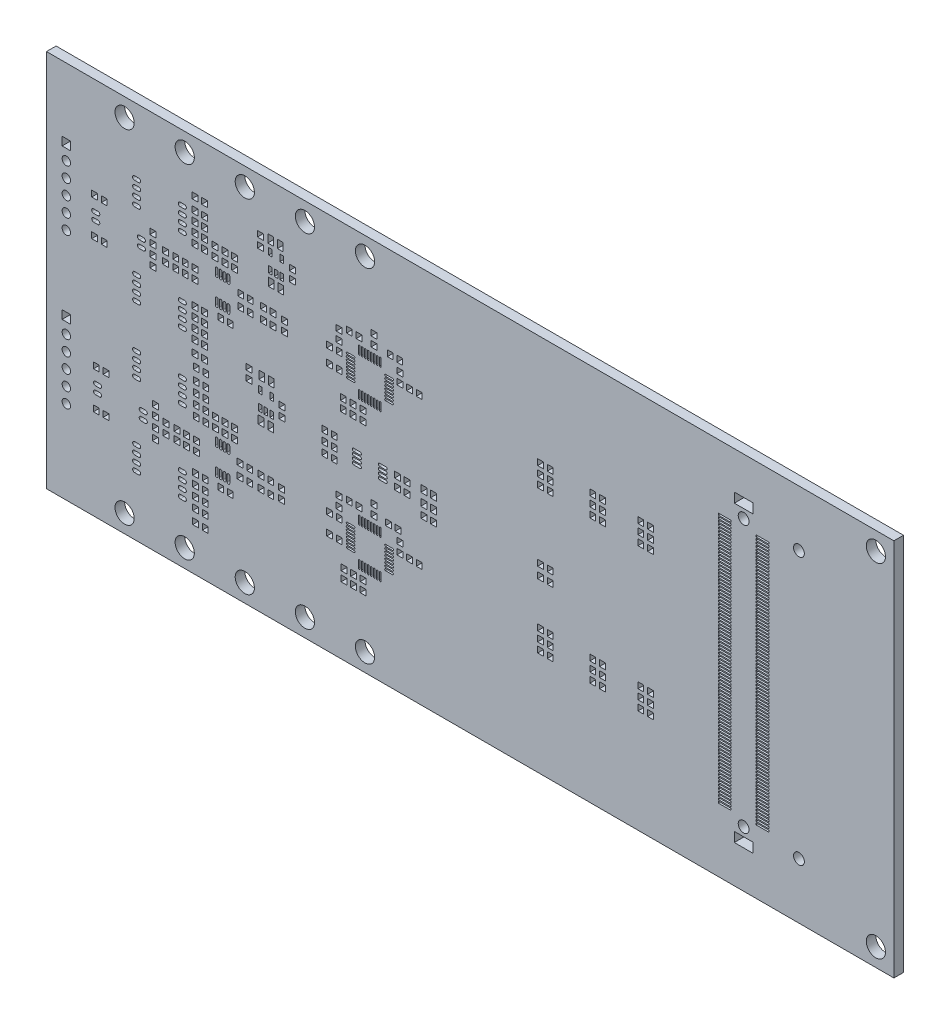
SolidWorks part; units mm, degrees
ref_plane "Front Plane" through (0, 0, 0) normal (0, 0, 1) x (1, 0, 0)
ref_plane "Top Plane" through (0, 0, 0) normal (0, 1, 0) x (1, 0, 0)
ref_plane "Right Plane" through (0, 0, 0) normal (1, 0, 0) x (0, 0, -1)
sketch "Model" plane through (0, 0, 0) normal (0, 0, 1) x (1, 0, 0)
  line L0 (-47.925, 52.1) -> (-47.925, 52.4)
  line L1 (-47.925, 52.4) -> (-45.775, 52.4)
  line L2 (-45.775, 52.4) -> (-45.775, 52.1)
  line L3 (-45.775, 52.1) -> (-47.925, 52.1)
  line L4 (-47.925, 51.6) -> (-47.925, 51.9)
  line L5 (-47.925, 51.9) -> (-45.775, 51.9)
  line L6 (-45.775, 51.9) -> (-45.775, 51.6)
  line L7 (-45.775, 51.6) -> (-47.925, 51.6)
  line L8 (-47.925, 51.1) -> (-47.925, 51.4)
  line L9 (-47.925, 51.4) -> (-45.775, 51.4)
  line L10 (-45.775, 51.4) -> (-45.775, 51.1)
  line L11 (-45.775, 51.1) -> (-47.925, 51.1)
  line L12 (-47.925, 50.6) -> (-47.925, 50.9)
  line L13 (-47.925, 50.9) -> (-45.775, 50.9)
  line L14 (-45.775, 50.9) -> (-45.775, 50.6)
  line L15 (-45.775, 50.6) -> (-47.925, 50.6)
  line L16 (-47.925, 50.1) -> (-47.925, 50.4)
  line L17 (-47.925, 50.4) -> (-45.775, 50.4)
  line L18 (-45.775, 50.4) -> (-45.775, 50.1)
  line L19 (-45.775, 50.1) -> (-47.925, 50.1)
  line L20 (-47.925, 49.6) -> (-47.925, 49.9)
  line L21 (-47.925, 49.9) -> (-45.775, 49.9)
  line L22 (-45.775, 49.9) -> (-45.775, 49.6)
  line L23 (-45.775, 49.6) -> (-47.925, 49.6)
  line L24 (-47.925, 49.1) -> (-47.925, 49.4)
  line L25 (-47.925, 49.4) -> (-45.775, 49.4)
  line L26 (-45.775, 49.4) -> (-45.775, 49.1)
  line L27 (-45.775, 49.1) -> (-47.925, 49.1)
  line L28 (-47.925, 48.6) -> (-47.925, 48.9)
  line L29 (-47.925, 48.9) -> (-45.775, 48.9)
  line L30 (-45.775, 48.9) -> (-45.775, 48.6)
  line L31 (-45.775, 48.6) -> (-47.925, 48.6)
  line L32 (-47.925, 48.1) -> (-47.925, 48.4)
  line L33 (-47.925, 48.4) -> (-45.775, 48.4)
  line L34 (-45.775, 48.4) -> (-45.775, 48.1)
  line L35 (-45.775, 48.1) -> (-47.925, 48.1)
  line L36 (-47.925, 47.6) -> (-47.925, 47.9)
  line L37 (-47.925, 47.9) -> (-45.775, 47.9)
  line L38 (-45.775, 47.9) -> (-45.775, 47.6)
  line L39 (-45.775, 47.6) -> (-47.925, 47.6)
  line L40 (-47.925, 47.1) -> (-47.925, 47.4)
  line L41 (-47.925, 47.4) -> (-45.775, 47.4)
  line L42 (-45.775, 47.4) -> (-45.775, 47.1)
  line L43 (-45.775, 47.1) -> (-47.925, 47.1)
  line L44 (-47.925, 46.6) -> (-47.925, 46.9)
  line L45 (-47.925, 46.9) -> (-45.775, 46.9)
  line L46 (-45.775, 46.9) -> (-45.775, 46.6)
  line L47 (-45.775, 46.6) -> (-47.925, 46.6)
  line L48 (-47.925, 46.1) -> (-47.925, 46.4)
  line L49 (-47.925, 46.4) -> (-45.775, 46.4)
  line L50 (-45.775, 46.4) -> (-45.775, 46.1)
  line L51 (-45.775, 46.1) -> (-47.925, 46.1)
  line L52 (-47.925, 45.6) -> (-47.925, 45.9)
  line L53 (-47.925, 45.9) -> (-45.775, 45.9)
  line L54 (-45.775, 45.9) -> (-45.775, 45.6)
  line L55 (-45.775, 45.6) -> (-47.925, 45.6)
  line L56 (-47.925, 45.1) -> (-47.925, 45.4)
  line L57 (-47.925, 45.4) -> (-45.775, 45.4)
  line L58 (-45.775, 45.4) -> (-45.775, 45.1)
  line L59 (-45.775, 45.1) -> (-47.925, 45.1)
  line L60 (-47.925, 44.6) -> (-47.925, 44.9)
  line L61 (-47.925, 44.9) -> (-45.775, 44.9)
  line L62 (-45.775, 44.9) -> (-45.775, 44.6)
  line L63 (-45.775, 44.6) -> (-47.925, 44.6)
  line L64 (-47.925, 44.1) -> (-47.925, 44.4)
  line L65 (-47.925, 44.4) -> (-45.775, 44.4)
  line L66 (-45.775, 44.4) -> (-45.775, 44.1)
  line L67 (-45.775, 44.1) -> (-47.925, 44.1)
  line L68 (-47.925, 43.6) -> (-47.925, 43.9)
  line L69 (-47.925, 43.9) -> (-45.775, 43.9)
  line L70 (-45.775, 43.9) -> (-45.775, 43.6)
  line L71 (-45.775, 43.6) -> (-47.925, 43.6)
  line L72 (-47.925, 43.1) -> (-47.925, 43.4)
  line L73 (-47.925, 43.4) -> (-45.775, 43.4)
  line L74 (-45.775, 43.4) -> (-45.775, 43.1)
  line L75 (-45.775, 43.1) -> (-47.925, 43.1)
  line L76 (-47.925, 42.6) -> (-47.925, 42.9)
  line L77 (-47.925, 42.9) -> (-45.775, 42.9)
  line L78 (-45.775, 42.9) -> (-45.775, 42.6)
  line L79 (-45.775, 42.6) -> (-47.925, 42.6)
  line L80 (-47.925, 42.1) -> (-47.925, 42.4)
  line L81 (-47.925, 42.4) -> (-45.775, 42.4)
  line L82 (-45.775, 42.4) -> (-45.775, 42.1)
  line L83 (-45.775, 42.1) -> (-47.925, 42.1)
  line L84 (-47.925, 41.6) -> (-47.925, 41.9)
  line L85 (-47.925, 41.9) -> (-45.775, 41.9)
  line L86 (-45.775, 41.9) -> (-45.775, 41.6)
  line L87 (-45.775, 41.6) -> (-47.925, 41.6)
  line L88 (-47.925, 41.1) -> (-47.925, 41.4)
  line L89 (-47.925, 41.4) -> (-45.775, 41.4)
  line L90 (-45.775, 41.4) -> (-45.775, 41.1)
  line L91 (-45.775, 41.1) -> (-47.925, 41.1)
  line L92 (-47.925, 40.6) -> (-47.925, 40.9)
  line L93 (-47.925, 40.9) -> (-45.775, 40.9)
  line L94 (-45.775, 40.9) -> (-45.775, 40.6)
  line L95 (-45.775, 40.6) -> (-47.925, 40.6)
  line L96 (-47.925, 40.1) -> (-47.925, 40.4)
  line L97 (-47.925, 40.4) -> (-45.775, 40.4)
  line L98 (-45.775, 40.4) -> (-45.775, 40.1)
  line L99 (-45.775, 40.1) -> (-47.925, 40.1)
  line L100 (-47.925, 39.6) -> (-47.925, 39.9)
  line L101 (-47.925, 39.9) -> (-45.775, 39.9)
  line L102 (-45.775, 39.9) -> (-45.775, 39.6)
  line L103 (-45.775, 39.6) -> (-47.925, 39.6)
  line L104 (-47.925, 39.1) -> (-47.925, 39.4)
  line L105 (-47.925, 39.4) -> (-45.775, 39.4)
  line L106 (-45.775, 39.4) -> (-45.775, 39.1)
  line L107 (-45.775, 39.1) -> (-47.925, 39.1)
  line L108 (-47.925, 38.6) -> (-47.925, 38.9)
  line L109 (-47.925, 38.9) -> (-45.775, 38.9)
  line L110 (-45.775, 38.9) -> (-45.775, 38.6)
  line L111 (-45.775, 38.6) -> (-47.925, 38.6)
  line L112 (-47.925, 38.1) -> (-47.925, 38.4)
  line L113 (-47.925, 38.4) -> (-45.775, 38.4)
  line L114 (-45.775, 38.4) -> (-45.775, 38.1)
  line L115 (-45.775, 38.1) -> (-47.925, 38.1)
  line L116 (-47.925, 37.6) -> (-47.925, 37.9)
  line L117 (-47.925, 37.9) -> (-45.775, 37.9)
  line L118 (-45.775, 37.9) -> (-45.775, 37.6)
  line L119 (-45.775, 37.6) -> (-47.925, 37.6)
  line L120 (-47.925, 37.1) -> (-47.925, 37.4)
  line L121 (-47.925, 37.4) -> (-45.775, 37.4)
  line L122 (-45.775, 37.4) -> (-45.775, 37.1)
  line L123 (-45.775, 37.1) -> (-47.925, 37.1)
  line L124 (-47.925, 36.6) -> (-47.925, 36.9)
  line L125 (-47.925, 36.9) -> (-45.775, 36.9)
  line L126 (-45.775, 36.9) -> (-45.775, 36.6)
  line L127 (-45.775, 36.6) -> (-47.925, 36.6)
  line L128 (-47.925, 36.1) -> (-47.925, 36.4)
  line L129 (-47.925, 36.4) -> (-45.775, 36.4)
  line L130 (-45.775, 36.4) -> (-45.775, 36.1)
  line L131 (-45.775, 36.1) -> (-47.925, 36.1)
  line L132 (-47.925, 35.6) -> (-47.925, 35.9)
  line L133 (-47.925, 35.9) -> (-45.775, 35.9)
  line L134 (-45.775, 35.9) -> (-45.775, 35.6)
  line L135 (-45.775, 35.6) -> (-47.925, 35.6)
  line L136 (-47.925, 35.1) -> (-47.925, 35.4)
  line L137 (-47.925, 35.4) -> (-45.775, 35.4)
  line L138 (-45.775, 35.4) -> (-45.775, 35.1)
  line L139 (-45.775, 35.1) -> (-47.925, 35.1)
  line L140 (-47.925, 34.6) -> (-47.925, 34.9)
  line L141 (-47.925, 34.9) -> (-45.775, 34.9)
  line L142 (-45.775, 34.9) -> (-45.775, 34.6)
  line L143 (-45.775, 34.6) -> (-47.925, 34.6)
  line L144 (-47.925, 34.1) -> (-47.925, 34.4)
  line L145 (-47.925, 34.4) -> (-45.775, 34.4)
  line L146 (-45.775, 34.4) -> (-45.775, 34.1)
  line L147 (-45.775, 34.1) -> (-47.925, 34.1)
  line L148 (-47.925, 33.6) -> (-47.925, 33.9)
  line L149 (-47.925, 33.9) -> (-45.775, 33.9)
  line L150 (-45.775, 33.9) -> (-45.775, 33.6)
  line L151 (-45.775, 33.6) -> (-47.925, 33.6)
  line L152 (-47.925, 33.1) -> (-47.925, 33.4)
  line L153 (-47.925, 33.4) -> (-45.775, 33.4)
  line L154 (-45.775, 33.4) -> (-45.775, 33.1)
  line L155 (-45.775, 33.1) -> (-47.925, 33.1)
  line L156 (-47.925, 32.6) -> (-47.925, 32.9)
  line L157 (-47.925, 32.9) -> (-45.775, 32.9)
  line L158 (-45.775, 32.9) -> (-45.775, 32.6)
  line L159 (-45.775, 32.6) -> (-47.925, 32.6)
  line L160 (-47.925, 32.1) -> (-47.925, 32.4)
  line L161 (-47.925, 32.4) -> (-45.775, 32.4)
  line L162 (-45.775, 32.4) -> (-45.775, 32.1)
  line L163 (-45.775, 32.1) -> (-47.925, 32.1)
  line L164 (-47.925, 31.6) -> (-47.925, 31.9)
  line L165 (-47.925, 31.9) -> (-45.775, 31.9)
  line L166 (-45.775, 31.9) -> (-45.775, 31.6)
  line L167 (-45.775, 31.6) -> (-47.925, 31.6)
  line L168 (-47.925, 31.1) -> (-47.925, 31.4)
  line L169 (-47.925, 31.4) -> (-45.775, 31.4)
  line L170 (-45.775, 31.4) -> (-45.775, 31.1)
  line L171 (-45.775, 31.1) -> (-47.925, 31.1)
  line L172 (-47.925, 30.6) -> (-47.925, 30.9)
  line L173 (-47.925, 30.9) -> (-45.775, 30.9)
  line L174 (-45.775, 30.9) -> (-45.775, 30.6)
  line L175 (-45.775, 30.6) -> (-47.925, 30.6)
  line L176 (-47.925, 30.1) -> (-47.925, 30.4)
  line L177 (-47.925, 30.4) -> (-45.775, 30.4)
  line L178 (-45.775, 30.4) -> (-45.775, 30.1)
  line L179 (-45.775, 30.1) -> (-47.925, 30.1)
  line L180 (-47.925, 29.6) -> (-47.925, 29.9)
  line L181 (-47.925, 29.9) -> (-45.775, 29.9)
  line L182 (-45.775, 29.9) -> (-45.775, 29.6)
  line L183 (-45.775, 29.6) -> (-47.925, 29.6)
  line L184 (-47.925, 29.1) -> (-47.925, 29.4)
  line L185 (-47.925, 29.4) -> (-45.775, 29.4)
  line L186 (-45.775, 29.4) -> (-45.775, 29.1)
  line L187 (-45.775, 29.1) -> (-47.925, 29.1)
  line L188 (-47.925, 28.6) -> (-47.925, 28.9)
  line L189 (-47.925, 28.9) -> (-45.775, 28.9)
  line L190 (-45.775, 28.9) -> (-45.775, 28.6)
  line L191 (-45.775, 28.6) -> (-47.925, 28.6)
  line L192 (-47.925, 28.1) -> (-47.925, 28.4)
  line L193 (-47.925, 28.4) -> (-45.775, 28.4)
  line L194 (-45.775, 28.4) -> (-45.775, 28.1)
  line L195 (-45.775, 28.1) -> (-47.925, 28.1)
  line L196 (-47.925, 27.6) -> (-47.925, 27.9)
  line L197 (-47.925, 27.9) -> (-45.775, 27.9)
  line L198 (-45.775, 27.9) -> (-45.775, 27.6)
  line L199 (-45.775, 27.6) -> (-47.925, 27.6)
  line L200 (-47.925, 27.1) -> (-47.925, 27.4)
  line L201 (-47.925, 27.4) -> (-45.775, 27.4)
  line L202 (-45.775, 27.4) -> (-45.775, 27.1)
  line L203 (-45.775, 27.1) -> (-47.925, 27.1)
  line L204 (-47.925, 26.6) -> (-47.925, 26.9)
  line L205 (-47.925, 26.9) -> (-45.775, 26.9)
  line L206 (-45.775, 26.9) -> (-45.775, 26.6)
  line L207 (-45.775, 26.6) -> (-47.925, 26.6)
  line L208 (-47.925, 26.1) -> (-47.925, 26.4)
  line L209 (-47.925, 26.4) -> (-45.775, 26.4)
  line L210 (-45.775, 26.4) -> (-45.775, 26.1)
  line L211 (-45.775, 26.1) -> (-47.925, 26.1)
  line L212 (-47.925, 25.6) -> (-47.925, 25.9)
  line L213 (-47.925, 25.9) -> (-45.775, 25.9)
  line L214 (-45.775, 25.9) -> (-45.775, 25.6)
  line L215 (-45.775, 25.6) -> (-47.925, 25.6)
  line L216 (-47.925, 25.1) -> (-47.925, 25.4)
  line L217 (-47.925, 25.4) -> (-45.775, 25.4)
  line L218 (-45.775, 25.4) -> (-45.775, 25.1)
  line L219 (-45.775, 25.1) -> (-47.925, 25.1)
  line L220 (-47.925, 24.6) -> (-47.925, 24.9)
  line L221 (-47.925, 24.9) -> (-45.775, 24.9)
  line L222 (-45.775, 24.9) -> (-45.775, 24.6)
  line L223 (-45.775, 24.6) -> (-47.925, 24.6)
  line L224 (-47.925, 24.1) -> (-47.925, 24.4)
  line L225 (-47.925, 24.4) -> (-45.775, 24.4)
  line L226 (-45.775, 24.4) -> (-45.775, 24.1)
  line L227 (-45.775, 24.1) -> (-47.925, 24.1)
  line L228 (-47.925, 23.6) -> (-47.925, 23.9)
  line L229 (-47.925, 23.9) -> (-45.775, 23.9)
  line L230 (-45.775, 23.9) -> (-45.775, 23.6)
  line L231 (-45.775, 23.6) -> (-47.925, 23.6)
  line L232 (-47.925, 23.1) -> (-47.925, 23.4)
  line L233 (-47.925, 23.4) -> (-45.775, 23.4)
  line L234 (-45.775, 23.4) -> (-45.775, 23.1)
  line L235 (-45.775, 23.1) -> (-47.925, 23.1)
  line L236 (-47.925, 22.6) -> (-47.925, 22.9)
  line L237 (-47.925, 22.9) -> (-45.775, 22.9)
  line L238 (-45.775, 22.9) -> (-45.775, 22.6)
  line L239 (-45.775, 22.6) -> (-47.925, 22.6)
  line L240 (-47.925, 22.1) -> (-47.925, 22.4)
  line L241 (-47.925, 22.4) -> (-45.775, 22.4)
  line L242 (-45.775, 22.4) -> (-45.775, 22.1)
  line L243 (-45.775, 22.1) -> (-47.925, 22.1)
  line L244 (-47.925, 21.6) -> (-47.925, 21.9)
  line L245 (-47.925, 21.9) -> (-45.775, 21.9)
  line L246 (-45.775, 21.9) -> (-45.775, 21.6)
  line L247 (-45.775, 21.6) -> (-47.925, 21.6)
  line L248 (-47.925, 21.1) -> (-47.925, 21.4)
  line L249 (-47.925, 21.4) -> (-45.775, 21.4)
  line L250 (-45.775, 21.4) -> (-45.775, 21.1)
  line L251 (-45.775, 21.1) -> (-47.925, 21.1)
  line L252 (-47.925, 20.6) -> (-47.925, 20.9)
  line L253 (-47.925, 20.9) -> (-45.775, 20.9)
  line L254 (-45.775, 20.9) -> (-45.775, 20.6)
  line L255 (-45.775, 20.6) -> (-47.925, 20.6)
  line L256 (-47.925, 20.1) -> (-47.925, 20.4)
  line L257 (-47.925, 20.4) -> (-45.775, 20.4)
  line L258 (-45.775, 20.4) -> (-45.775, 20.1)
  line L259 (-45.775, 20.1) -> (-47.925, 20.1)
  line L260 (-47.925, 19.6) -> (-47.925, 19.9)
  line L261 (-47.925, 19.9) -> (-45.775, 19.9)
  line L262 (-45.775, 19.9) -> (-45.775, 19.6)
  line L263 (-45.775, 19.6) -> (-47.925, 19.6)
  line L264 (-47.925, 19.1) -> (-47.925, 19.4)
  line L265 (-47.925, 19.4) -> (-45.775, 19.4)
  line L266 (-45.775, 19.4) -> (-45.775, 19.1)
  line L267 (-45.775, 19.1) -> (-47.925, 19.1)
  line L268 (-47.925, 18.6) -> (-47.925, 18.9)
  line L269 (-47.925, 18.9) -> (-45.775, 18.9)
  line L270 (-45.775, 18.9) -> (-45.775, 18.6)
  line L271 (-45.775, 18.6) -> (-47.925, 18.6)
  line L272 (-47.925, 18.1) -> (-47.925, 18.4)
  line L273 (-47.925, 18.4) -> (-45.775, 18.4)
  line L274 (-45.775, 18.4) -> (-45.775, 18.1)
  line L275 (-45.775, 18.1) -> (-47.925, 18.1)
  line L276 (-47.925, 17.6) -> (-47.925, 17.9)
  line L277 (-47.925, 17.9) -> (-45.775, 17.9)
  line L278 (-45.775, 17.9) -> (-45.775, 17.6)
  line L279 (-45.775, 17.6) -> (-47.925, 17.6)
  line L280 (-47.925, 17.1) -> (-47.925, 17.4)
  line L281 (-47.925, 17.4) -> (-45.775, 17.4)
  line L282 (-45.775, 17.4) -> (-45.775, 17.1)
  line L283 (-45.775, 17.1) -> (-47.925, 17.1)
  line L284 (-47.925, 16.6) -> (-47.925, 16.9)
  line L285 (-47.925, 16.9) -> (-45.775, 16.9)
  line L286 (-45.775, 16.9) -> (-45.775, 16.6)
  line L287 (-45.775, 16.6) -> (-47.925, 16.6)
  line L288 (-47.925, 16.1) -> (-47.925, 16.4)
  line L289 (-47.925, 16.4) -> (-45.775, 16.4)
  line L290 (-45.775, 16.4) -> (-45.775, 16.1)
  line L291 (-45.775, 16.1) -> (-47.925, 16.1)
  line L292 (-47.925, 15.6) -> (-47.925, 15.9)
  line L293 (-47.925, 15.9) -> (-45.775, 15.9)
  line L294 (-45.775, 15.9) -> (-45.775, 15.6)
  line L295 (-45.775, 15.6) -> (-47.925, 15.6)
  line L296 (-47.925, 15.1) -> (-47.925, 15.4)
  line L297 (-47.925, 15.4) -> (-45.775, 15.4)
  line L298 (-45.775, 15.4) -> (-45.775, 15.1)
  line L299 (-45.775, 15.1) -> (-47.925, 15.1)
  line L300 (-47.925, 14.6) -> (-47.925, 14.9)
  line L301 (-47.925, 14.9) -> (-45.775, 14.9)
  line L302 (-45.775, 14.9) -> (-45.775, 14.6)
  line L303 (-45.775, 14.6) -> (-47.925, 14.6)
  line L304 (-47.925, 14.1) -> (-47.925, 14.4)
  line L305 (-47.925, 14.4) -> (-45.775, 14.4)
  line L306 (-45.775, 14.4) -> (-45.775, 14.1)
  line L307 (-45.775, 14.1) -> (-47.925, 14.1)
  line L308 (-47.925, 13.6) -> (-47.925, 13.9)
  line L309 (-47.925, 13.9) -> (-45.775, 13.9)
  line L310 (-45.775, 13.9) -> (-45.775, 13.6)
  line L311 (-45.775, 13.6) -> (-47.925, 13.6)
  line L312 (-47.925, 13.1) -> (-47.925, 13.4)
  line L313 (-47.925, 13.4) -> (-45.775, 13.4)
  line L314 (-45.775, 13.4) -> (-45.775, 13.1)
  line L315 (-45.775, 13.1) -> (-47.925, 13.1)
  line L316 (-47.925, 12.6) -> (-47.925, 12.9)
  line L317 (-47.925, 12.9) -> (-45.775, 12.9)
  line L318 (-45.775, 12.9) -> (-45.775, 12.6)
  line L319 (-45.775, 12.6) -> (-47.925, 12.6)
  line L320 (-47.925, 12.1) -> (-47.925, 12.4)
  line L321 (-47.925, 12.4) -> (-45.775, 12.4)
  line L322 (-45.775, 12.4) -> (-45.775, 12.1)
  line L323 (-45.775, 12.1) -> (-47.925, 12.1)
  line L324 (-47.925, 11.6) -> (-47.925, 11.9)
  line L325 (-47.925, 11.9) -> (-45.775, 11.9)
  line L326 (-45.775, 11.9) -> (-45.775, 11.6)
  line L327 (-45.775, 11.6) -> (-47.925, 11.6)
  line L328 (-47.925, 11.1) -> (-47.925, 11.4)
  line L329 (-47.925, 11.4) -> (-45.775, 11.4)
  line L330 (-45.775, 11.4) -> (-45.775, 11.1)
  line L331 (-45.775, 11.1) -> (-47.925, 11.1)
  line L332 (-47.925, 10.6) -> (-47.925, 10.9)
  line L333 (-47.925, 10.9) -> (-45.775, 10.9)
  line L334 (-45.775, 10.9) -> (-45.775, 10.6)
  line L335 (-45.775, 10.6) -> (-47.925, 10.6)
  line L336 (-54.225, 10.6) -> (-54.225, 10.9)
  line L337 (-54.225, 10.9) -> (-52.075, 10.9)
  line L338 (-52.075, 10.9) -> (-52.075, 10.6)
  line L339 (-52.075, 10.6) -> (-54.225, 10.6)
  line L340 (-54.225, 11.1) -> (-54.225, 11.4)
  line L341 (-54.225, 11.4) -> (-52.075, 11.4)
  line L342 (-52.075, 11.4) -> (-52.075, 11.1)
  line L343 (-52.075, 11.1) -> (-54.225, 11.1)
  line L344 (-54.225, 11.6) -> (-54.225, 11.9)
  line L345 (-54.225, 11.9) -> (-52.075, 11.9)
  line L346 (-52.075, 11.9) -> (-52.075, 11.6)
  line L347 (-52.075, 11.6) -> (-54.225, 11.6)
  line L348 (-54.225, 12.1) -> (-54.225, 12.4)
  line L349 (-54.225, 12.4) -> (-52.075, 12.4)
  line L350 (-52.075, 12.4) -> (-52.075, 12.1)
  line L351 (-52.075, 12.1) -> (-54.225, 12.1)
  line L352 (-54.225, 12.6) -> (-54.225, 12.9)
  line L353 (-54.225, 12.9) -> (-52.075, 12.9)
  line L354 (-52.075, 12.9) -> (-52.075, 12.6)
  line L355 (-52.075, 12.6) -> (-54.225, 12.6)
  line L356 (-54.225, 13.1) -> (-54.225, 13.4)
  line L357 (-54.225, 13.4) -> (-52.075, 13.4)
  line L358 (-52.075, 13.4) -> (-52.075, 13.1)
  line L359 (-52.075, 13.1) -> (-54.225, 13.1)
  line L360 (-54.225, 13.6) -> (-54.225, 13.9)
  line L361 (-54.225, 13.9) -> (-52.075, 13.9)
  line L362 (-52.075, 13.9) -> (-52.075, 13.6)
  line L363 (-52.075, 13.6) -> (-54.225, 13.6)
  line L364 (-54.225, 14.1) -> (-54.225, 14.4)
  line L365 (-54.225, 14.4) -> (-52.075, 14.4)
  line L366 (-52.075, 14.4) -> (-52.075, 14.1)
  line L367 (-52.075, 14.1) -> (-54.225, 14.1)
  line L368 (-54.225, 14.6) -> (-54.225, 14.9)
  line L369 (-54.225, 14.9) -> (-52.075, 14.9)
  line L370 (-52.075, 14.9) -> (-52.075, 14.6)
  line L371 (-52.075, 14.6) -> (-54.225, 14.6)
  line L372 (-54.225, 15.1) -> (-54.225, 15.4)
  line L373 (-54.225, 15.4) -> (-52.075, 15.4)
  line L374 (-52.075, 15.4) -> (-52.075, 15.1)
  line L375 (-52.075, 15.1) -> (-54.225, 15.1)
  line L376 (-54.225, 15.6) -> (-54.225, 15.9)
  line L377 (-54.225, 15.9) -> (-52.075, 15.9)
  line L378 (-52.075, 15.9) -> (-52.075, 15.6)
  line L379 (-52.075, 15.6) -> (-54.225, 15.6)
  line L380 (-54.225, 16.1) -> (-54.225, 16.4)
  line L381 (-54.225, 16.4) -> (-52.075, 16.4)
  line L382 (-52.075, 16.4) -> (-52.075, 16.1)
  line L383 (-52.075, 16.1) -> (-54.225, 16.1)
  line L384 (-54.225, 16.6) -> (-54.225, 16.9)
  line L385 (-54.225, 16.9) -> (-52.075, 16.9)
  line L386 (-52.075, 16.9) -> (-52.075, 16.6)
  line L387 (-52.075, 16.6) -> (-54.225, 16.6)
  line L388 (-54.225, 17.1) -> (-54.225, 17.4)
  line L389 (-54.225, 17.4) -> (-52.075, 17.4)
  line L390 (-52.075, 17.4) -> (-52.075, 17.1)
  line L391 (-52.075, 17.1) -> (-54.225, 17.1)
  line L392 (-54.225, 17.6) -> (-54.225, 17.9)
  line L393 (-54.225, 17.9) -> (-52.075, 17.9)
  line L394 (-52.075, 17.9) -> (-52.075, 17.6)
  line L395 (-52.075, 17.6) -> (-54.225, 17.6)
  line L396 (-54.225, 18.1) -> (-54.225, 18.4)
  line L397 (-54.225, 18.4) -> (-52.075, 18.4)
  line L398 (-52.075, 18.4) -> (-52.075, 18.1)
  line L399 (-52.075, 18.1) -> (-54.225, 18.1)
  line L400 (-54.225, 18.6) -> (-54.225, 18.9)
  line L401 (-54.225, 18.9) -> (-52.075, 18.9)
  line L402 (-52.075, 18.9) -> (-52.075, 18.6)
  line L403 (-52.075, 18.6) -> (-54.225, 18.6)
  line L404 (-54.225, 19.1) -> (-54.225, 19.4)
  line L405 (-54.225, 19.4) -> (-52.075, 19.4)
  line L406 (-52.075, 19.4) -> (-52.075, 19.1)
  line L407 (-52.075, 19.1) -> (-54.225, 19.1)
  line L408 (-54.225, 19.6) -> (-54.225, 19.9)
  line L409 (-54.225, 19.9) -> (-52.075, 19.9)
  line L410 (-52.075, 19.9) -> (-52.075, 19.6)
  line L411 (-52.075, 19.6) -> (-54.225, 19.6)
  line L412 (-54.225, 20.1) -> (-54.225, 20.4)
  line L413 (-54.225, 20.4) -> (-52.075, 20.4)
  line L414 (-52.075, 20.4) -> (-52.075, 20.1)
  line L415 (-52.075, 20.1) -> (-54.225, 20.1)
  line L416 (-54.225, 20.6) -> (-54.225, 20.9)
  line L417 (-54.225, 20.9) -> (-52.075, 20.9)
  line L418 (-52.075, 20.9) -> (-52.075, 20.6)
  line L419 (-52.075, 20.6) -> (-54.225, 20.6)
  line L420 (-54.225, 21.1) -> (-54.225, 21.4)
  line L421 (-54.225, 21.4) -> (-52.075, 21.4)
  line L422 (-52.075, 21.4) -> (-52.075, 21.1)
  line L423 (-52.075, 21.1) -> (-54.225, 21.1)
  line L424 (-54.225, 21.6) -> (-54.225, 21.9)
  line L425 (-54.225, 21.9) -> (-52.075, 21.9)
  line L426 (-52.075, 21.9) -> (-52.075, 21.6)
  line L427 (-52.075, 21.6) -> (-54.225, 21.6)
  line L428 (-54.225, 22.1) -> (-54.225, 22.4)
  line L429 (-54.225, 22.4) -> (-52.075, 22.4)
  line L430 (-52.075, 22.4) -> (-52.075, 22.1)
  line L431 (-52.075, 22.1) -> (-54.225, 22.1)
  line L432 (-54.225, 22.6) -> (-54.225, 22.9)
  line L433 (-54.225, 22.9) -> (-52.075, 22.9)
  line L434 (-52.075, 22.9) -> (-52.075, 22.6)
  line L435 (-52.075, 22.6) -> (-54.225, 22.6)
  line L436 (-54.225, 23.1) -> (-54.225, 23.4)
  line L437 (-54.225, 23.4) -> (-52.075, 23.4)
  line L438 (-52.075, 23.4) -> (-52.075, 23.1)
  line L439 (-52.075, 23.1) -> (-54.225, 23.1)
  line L440 (-54.225, 23.6) -> (-54.225, 23.9)
  line L441 (-54.225, 23.9) -> (-52.075, 23.9)
  line L442 (-52.075, 23.9) -> (-52.075, 23.6)
  line L443 (-52.075, 23.6) -> (-54.225, 23.6)
  line L444 (-54.225, 24.1) -> (-54.225, 24.4)
  line L445 (-54.225, 24.4) -> (-52.075, 24.4)
  line L446 (-52.075, 24.4) -> (-52.075, 24.1)
  line L447 (-52.075, 24.1) -> (-54.225, 24.1)
  line L448 (-54.225, 24.6) -> (-54.225, 24.9)
  line L449 (-54.225, 24.9) -> (-52.075, 24.9)
  line L450 (-52.075, 24.9) -> (-52.075, 24.6)
  line L451 (-52.075, 24.6) -> (-54.225, 24.6)
  line L452 (-54.225, 25.1) -> (-54.225, 25.4)
  line L453 (-54.225, 25.4) -> (-52.075, 25.4)
  line L454 (-52.075, 25.4) -> (-52.075, 25.1)
  line L455 (-52.075, 25.1) -> (-54.225, 25.1)
  line L456 (-54.225, 25.6) -> (-54.225, 25.9)
  line L457 (-54.225, 25.9) -> (-52.075, 25.9)
  line L458 (-52.075, 25.9) -> (-52.075, 25.6)
  line L459 (-52.075, 25.6) -> (-54.225, 25.6)
  line L460 (-54.225, 26.1) -> (-54.225, 26.4)
  line L461 (-54.225, 26.4) -> (-52.075, 26.4)
  line L462 (-52.075, 26.4) -> (-52.075, 26.1)
  line L463 (-52.075, 26.1) -> (-54.225, 26.1)
  line L464 (-54.225, 26.6) -> (-54.225, 26.9)
  line L465 (-54.225, 26.9) -> (-52.075, 26.9)
  line L466 (-52.075, 26.9) -> (-52.075, 26.6)
  line L467 (-52.075, 26.6) -> (-54.225, 26.6)
  line L468 (-54.225, 27.1) -> (-54.225, 27.4)
  line L469 (-54.225, 27.4) -> (-52.075, 27.4)
  line L470 (-52.075, 27.4) -> (-52.075, 27.1)
  line L471 (-52.075, 27.1) -> (-54.225, 27.1)
  line L472 (-54.225, 27.6) -> (-54.225, 27.9)
  line L473 (-54.225, 27.9) -> (-52.075, 27.9)
  line L474 (-52.075, 27.9) -> (-52.075, 27.6)
  line L475 (-52.075, 27.6) -> (-54.225, 27.6)
  line L476 (-54.225, 28.1) -> (-54.225, 28.4)
  line L477 (-54.225, 28.4) -> (-52.075, 28.4)
  line L478 (-52.075, 28.4) -> (-52.075, 28.1)
  line L479 (-52.075, 28.1) -> (-54.225, 28.1)
  line L480 (-54.225, 28.6) -> (-54.225, 28.9)
  line L481 (-54.225, 28.9) -> (-52.075, 28.9)
  line L482 (-52.075, 28.9) -> (-52.075, 28.6)
  line L483 (-52.075, 28.6) -> (-54.225, 28.6)
  line L484 (-54.225, 29.1) -> (-54.225, 29.4)
  line L485 (-54.225, 29.4) -> (-52.075, 29.4)
  line L486 (-52.075, 29.4) -> (-52.075, 29.1)
  line L487 (-52.075, 29.1) -> (-54.225, 29.1)
  line L488 (-54.225, 29.6) -> (-54.225, 29.9)
  line L489 (-54.225, 29.9) -> (-52.075, 29.9)
  line L490 (-52.075, 29.9) -> (-52.075, 29.6)
  line L491 (-52.075, 29.6) -> (-54.225, 29.6)
  line L492 (-54.225, 30.1) -> (-54.225, 30.4)
  line L493 (-54.225, 30.4) -> (-52.075, 30.4)
  line L494 (-52.075, 30.4) -> (-52.075, 30.1)
  line L495 (-52.075, 30.1) -> (-54.225, 30.1)
  line L496 (-54.225, 30.6) -> (-54.225, 30.9)
  line L497 (-54.225, 30.9) -> (-52.075, 30.9)
  line L498 (-52.075, 30.9) -> (-52.075, 30.6)
  line L499 (-52.075, 30.6) -> (-54.225, 30.6)
  line L500 (-54.225, 31.1) -> (-54.225, 31.4)
  line L501 (-54.225, 31.4) -> (-52.075, 31.4)
  line L502 (-52.075, 31.4) -> (-52.075, 31.1)
  line L503 (-52.075, 31.1) -> (-54.225, 31.1)
  line L504 (-54.225, 31.6) -> (-54.225, 31.9)
  line L505 (-54.225, 31.9) -> (-52.075, 31.9)
  line L506 (-52.075, 31.9) -> (-52.075, 31.6)
  line L507 (-52.075, 31.6) -> (-54.225, 31.6)
  line L508 (-54.225, 32.1) -> (-54.225, 32.4)
  line L509 (-54.225, 32.4) -> (-52.075, 32.4)
  line L510 (-52.075, 32.4) -> (-52.075, 32.1)
  line L511 (-52.075, 32.1) -> (-54.225, 32.1)
  line L512 (-54.225, 32.6) -> (-54.225, 32.9)
  line L513 (-54.225, 32.9) -> (-52.075, 32.9)
  line L514 (-52.075, 32.9) -> (-52.075, 32.6)
  line L515 (-52.075, 32.6) -> (-54.225, 32.6)
  line L516 (-54.225, 33.1) -> (-54.225, 33.4)
  line L517 (-54.225, 33.4) -> (-52.075, 33.4)
  line L518 (-52.075, 33.4) -> (-52.075, 33.1)
  line L519 (-52.075, 33.1) -> (-54.225, 33.1)
  line L520 (-54.225, 33.6) -> (-54.225, 33.9)
  line L521 (-54.225, 33.9) -> (-52.075, 33.9)
  line L522 (-52.075, 33.9) -> (-52.075, 33.6)
  line L523 (-52.075, 33.6) -> (-54.225, 33.6)
  line L524 (-54.225, 34.1) -> (-54.225, 34.4)
  line L525 (-54.225, 34.4) -> (-52.075, 34.4)
  line L526 (-52.075, 34.4) -> (-52.075, 34.1)
  line L527 (-52.075, 34.1) -> (-54.225, 34.1)
  line L528 (-54.225, 34.6) -> (-54.225, 34.9)
  line L529 (-54.225, 34.9) -> (-52.075, 34.9)
  line L530 (-52.075, 34.9) -> (-52.075, 34.6)
  line L531 (-52.075, 34.6) -> (-54.225, 34.6)
  line L532 (-54.225, 35.1) -> (-54.225, 35.4)
  line L533 (-54.225, 35.4) -> (-52.075, 35.4)
  line L534 (-52.075, 35.4) -> (-52.075, 35.1)
  line L535 (-52.075, 35.1) -> (-54.225, 35.1)
  line L536 (-54.225, 35.6) -> (-54.225, 35.9)
  line L537 (-54.225, 35.9) -> (-52.075, 35.9)
  line L538 (-52.075, 35.9) -> (-52.075, 35.6)
  line L539 (-52.075, 35.6) -> (-54.225, 35.6)
  line L540 (-54.225, 36.1) -> (-54.225, 36.4)
  line L541 (-54.225, 36.4) -> (-52.075, 36.4)
  line L542 (-52.075, 36.4) -> (-52.075, 36.1)
  line L543 (-52.075, 36.1) -> (-54.225, 36.1)
  line L544 (-54.225, 36.6) -> (-54.225, 36.9)
  line L545 (-54.225, 36.9) -> (-52.075, 36.9)
  line L546 (-52.075, 36.9) -> (-52.075, 36.6)
  line L547 (-52.075, 36.6) -> (-54.225, 36.6)
  line L548 (-54.225, 37.1) -> (-54.225, 37.4)
  line L549 (-54.225, 37.4) -> (-52.075, 37.4)
  line L550 (-52.075, 37.4) -> (-52.075, 37.1)
  line L551 (-52.075, 37.1) -> (-54.225, 37.1)
  line L552 (-54.225, 37.6) -> (-54.225, 37.9)
  line L553 (-54.225, 37.9) -> (-52.075, 37.9)
  line L554 (-52.075, 37.9) -> (-52.075, 37.6)
  line L555 (-52.075, 37.6) -> (-54.225, 37.6)
  line L556 (-54.225, 38.1) -> (-54.225, 38.4)
  line L557 (-54.225, 38.4) -> (-52.075, 38.4)
  line L558 (-52.075, 38.4) -> (-52.075, 38.1)
  line L559 (-52.075, 38.1) -> (-54.225, 38.1)
  line L560 (-54.225, 38.6) -> (-54.225, 38.9)
  line L561 (-54.225, 38.9) -> (-52.075, 38.9)
  line L562 (-52.075, 38.9) -> (-52.075, 38.6)
  line L563 (-52.075, 38.6) -> (-54.225, 38.6)
  line L564 (-54.225, 39.1) -> (-54.225, 39.4)
  line L565 (-54.225, 39.4) -> (-52.075, 39.4)
  line L566 (-52.075, 39.4) -> (-52.075, 39.1)
  line L567 (-52.075, 39.1) -> (-54.225, 39.1)
  line L568 (-54.225, 39.6) -> (-54.225, 39.9)
  line L569 (-54.225, 39.9) -> (-52.075, 39.9)
  line L570 (-52.075, 39.9) -> (-52.075, 39.6)
  line L571 (-52.075, 39.6) -> (-54.225, 39.6)
  line L572 (-54.225, 40.1) -> (-54.225, 40.4)
  line L573 (-54.225, 40.4) -> (-52.075, 40.4)
  line L574 (-52.075, 40.4) -> (-52.075, 40.1)
  line L575 (-52.075, 40.1) -> (-54.225, 40.1)
  line L576 (-54.225, 40.6) -> (-54.225, 40.9)
  line L577 (-54.225, 40.9) -> (-52.075, 40.9)
  line L578 (-52.075, 40.9) -> (-52.075, 40.6)
  line L579 (-52.075, 40.6) -> (-54.225, 40.6)
  line L580 (-54.225, 41.1) -> (-54.225, 41.4)
  line L581 (-54.225, 41.4) -> (-52.075, 41.4)
  line L582 (-52.075, 41.4) -> (-52.075, 41.1)
  line L583 (-52.075, 41.1) -> (-54.225, 41.1)
  line L584 (-54.225, 41.6) -> (-54.225, 41.9)
  line L585 (-54.225, 41.9) -> (-52.075, 41.9)
  line L586 (-52.075, 41.9) -> (-52.075, 41.6)
  line L587 (-52.075, 41.6) -> (-54.225, 41.6)
  line L588 (-54.225, 42.1) -> (-54.225, 42.4)
  line L589 (-54.225, 42.4) -> (-52.075, 42.4)
  line L590 (-52.075, 42.4) -> (-52.075, 42.1)
  line L591 (-52.075, 42.1) -> (-54.225, 42.1)
  line L592 (-54.225, 42.6) -> (-54.225, 42.9)
  line L593 (-54.225, 42.9) -> (-52.075, 42.9)
  line L594 (-52.075, 42.9) -> (-52.075, 42.6)
  line L595 (-52.075, 42.6) -> (-54.225, 42.6)
  line L596 (-54.225, 43.1) -> (-54.225, 43.4)
  line L597 (-54.225, 43.4) -> (-52.075, 43.4)
  line L598 (-52.075, 43.4) -> (-52.075, 43.1)
  line L599 (-52.075, 43.1) -> (-54.225, 43.1)
  line L600 (-54.225, 43.6) -> (-54.225, 43.9)
  line L601 (-54.225, 43.9) -> (-52.075, 43.9)
  line L602 (-52.075, 43.9) -> (-52.075, 43.6)
  line L603 (-52.075, 43.6) -> (-54.225, 43.6)
  line L604 (-54.225, 44.1) -> (-54.225, 44.4)
  line L605 (-54.225, 44.4) -> (-52.075, 44.4)
  line L606 (-52.075, 44.4) -> (-52.075, 44.1)
  line L607 (-52.075, 44.1) -> (-54.225, 44.1)
  line L608 (-54.225, 44.6) -> (-54.225, 44.9)
  line L609 (-54.225, 44.9) -> (-52.075, 44.9)
  line L610 (-52.075, 44.9) -> (-52.075, 44.6)
  line L611 (-52.075, 44.6) -> (-54.225, 44.6)
  line L612 (-54.225, 45.1) -> (-54.225, 45.4)
  line L613 (-54.225, 45.4) -> (-52.075, 45.4)
  line L614 (-52.075, 45.4) -> (-52.075, 45.1)
  line L615 (-52.075, 45.1) -> (-54.225, 45.1)
  line L616 (-54.225, 45.6) -> (-54.225, 45.9)
  line L617 (-54.225, 45.9) -> (-52.075, 45.9)
  line L618 (-52.075, 45.9) -> (-52.075, 45.6)
  line L619 (-52.075, 45.6) -> (-54.225, 45.6)
  line L620 (-54.225, 46.1) -> (-54.225, 46.4)
  line L621 (-54.225, 46.4) -> (-52.075, 46.4)
  line L622 (-52.075, 46.4) -> (-52.075, 46.1)
  line L623 (-52.075, 46.1) -> (-54.225, 46.1)
  line L624 (-54.225, 46.6) -> (-54.225, 46.9)
  line L625 (-54.225, 46.9) -> (-52.075, 46.9)
  line L626 (-52.075, 46.9) -> (-52.075, 46.6)
  line L627 (-52.075, 46.6) -> (-54.225, 46.6)
  line L628 (-54.225, 47.1) -> (-54.225, 47.4)
  line L629 (-54.225, 47.4) -> (-52.075, 47.4)
  line L630 (-52.075, 47.4) -> (-52.075, 47.1)
  line L631 (-52.075, 47.1) -> (-54.225, 47.1)
  line L632 (-54.225, 47.6) -> (-54.225, 47.9)
  line L633 (-54.225, 47.9) -> (-52.075, 47.9)
  line L634 (-52.075, 47.9) -> (-52.075, 47.6)
  line L635 (-52.075, 47.6) -> (-54.225, 47.6)
  line L636 (-54.225, 48.1) -> (-54.225, 48.4)
  line L637 (-54.225, 48.4) -> (-52.075, 48.4)
  line L638 (-52.075, 48.4) -> (-52.075, 48.1)
  line L639 (-52.075, 48.1) -> (-54.225, 48.1)
  line L640 (-54.225, 48.6) -> (-54.225, 48.9)
  line L641 (-54.225, 48.9) -> (-52.075, 48.9)
  line L642 (-52.075, 48.9) -> (-52.075, 48.6)
  line L643 (-52.075, 48.6) -> (-54.225, 48.6)
  line L644 (-54.225, 49.1) -> (-54.225, 49.4)
  line L645 (-54.225, 49.4) -> (-52.075, 49.4)
  line L646 (-52.075, 49.4) -> (-52.075, 49.1)
  line L647 (-52.075, 49.1) -> (-54.225, 49.1)
  line L648 (-54.225, 49.6) -> (-54.225, 49.9)
  line L649 (-54.225, 49.9) -> (-52.075, 49.9)
  line L650 (-52.075, 49.9) -> (-52.075, 49.6)
  line L651 (-52.075, 49.6) -> (-54.225, 49.6)
  line L652 (-54.225, 50.1) -> (-54.225, 50.4)
  line L653 (-54.225, 50.4) -> (-52.075, 50.4)
  line L654 (-52.075, 50.4) -> (-52.075, 50.1)
  line L655 (-52.075, 50.1) -> (-54.225, 50.1)
  line L656 (-54.225, 50.6) -> (-54.225, 50.9)
  line L657 (-54.225, 50.9) -> (-52.075, 50.9)
  line L658 (-52.075, 50.9) -> (-52.075, 50.6)
  line L659 (-52.075, 50.6) -> (-54.225, 50.6)
  line L660 (-54.225, 51.1) -> (-54.225, 51.4)
  line L661 (-54.225, 51.4) -> (-52.075, 51.4)
  line L662 (-52.075, 51.4) -> (-52.075, 51.1)
  line L663 (-52.075, 51.1) -> (-54.225, 51.1)
  line L664 (-54.225, 51.6) -> (-54.225, 51.9)
  line L665 (-54.225, 51.9) -> (-52.075, 51.9)
  line L666 (-52.075, 51.9) -> (-52.075, 51.6)
  line L667 (-52.075, 51.6) -> (-54.225, 51.6)
  line L668 (-54.225, 52.1) -> (-54.225, 52.4)
  line L669 (-54.225, 52.4) -> (-52.075, 52.4)
  line L670 (-52.075, 52.4) -> (-52.075, 52.1)
  line L671 (-52.075, 52.1) -> (-54.225, 52.1)
  line L672 (-48.45, 55.15) -> (-51.55, 55.15)
  line L673 (-51.55, 55.15) -> (-51.55, 56.75)
  line L674 (-51.55, 56.75) -> (-48.45, 56.75)
  line L675 (-48.45, 56.75) -> (-48.45, 55.15)
  line L676 (-48.45, 6.25) -> (-51.55, 6.25)
  line L677 (-51.55, 6.25) -> (-51.55, 7.85)
  line L678 (-51.55, 7.85) -> (-48.45, 7.85)
  line L679 (-48.45, 7.85) -> (-48.45, 6.25)
  line L680 (-102.675, 30.6249) -> (-103.725, 30.6249)
  line L681 (-103.725, 30.6249) -> (-103.725, 31.7751)
  line L682 (-103.725, 31.7751) -> (-102.675, 31.7751)
  line L683 (-102.675, 31.7751) -> (-102.675, 30.6249)
  line L684 (-102.675, 28.6249) -> (-103.725, 28.6249)
  line L685 (-103.725, 28.6249) -> (-103.725, 29.7751)
  line L686 (-103.725, 29.7751) -> (-102.675, 29.7751)
  line L687 (-102.675, 29.7751) -> (-102.675, 28.6249)
  line L688 (-101.075, 28.6249) -> (-102.125, 28.6249)
  line L689 (-102.125, 28.6249) -> (-102.125, 29.7751)
  line L690 (-102.125, 29.7751) -> (-101.075, 29.7751)
  line L691 (-101.075, 29.7751) -> (-101.075, 28.6249)
  line L692 (-101.075, 30.6249) -> (-102.125, 30.6249)
  line L693 (-102.125, 30.6249) -> (-102.125, 31.7751)
  line L694 (-102.125, 31.7751) -> (-101.075, 31.7751)
  line L695 (-101.075, 31.7751) -> (-101.075, 30.6249)
  line L696 (-150.65, 13.48) -> (-151.35, 13.48)
  line L697 (-151.35, 14.13) -> (-150.65, 14.13)
  line L698 (-150.65, 12.21) -> (-151.35, 12.21)
  line L699 (-151.35, 12.86) -> (-150.65, 12.86)
  line L700 (-150.65, 10.94) -> (-151.35, 10.94)
  line L701 (-151.35, 11.59) -> (-150.65, 11.59)
  line L702 (-150.65, 9.67) -> (-151.35, 9.67)
  line L703 (-151.35, 10.32) -> (-150.65, 10.32)
  line L704 (-143.05, 9.67) -> (-143.75, 9.67)
  line L705 (-143.75, 10.32) -> (-143.05, 10.32)
  line L706 (-143.05, 10.94) -> (-143.75, 10.94)
  line L707 (-143.75, 11.59) -> (-143.05, 11.59)
  line L708 (-143.05, 12.21) -> (-143.75, 12.21)
  line L709 (-143.75, 12.86) -> (-143.05, 12.86)
  line L710 (-143.05, 13.48) -> (-143.75, 13.48)
  line L711 (-143.75, 14.13) -> (-143.05, 14.13)
  line L712 (-150.65, 26.98) -> (-151.35, 26.98)
  line L713 (-151.35, 27.63) -> (-150.65, 27.63)
  line L714 (-150.65, 25.71) -> (-151.35, 25.71)
  line L715 (-151.35, 26.36) -> (-150.65, 26.36)
  line L716 (-150.65, 24.44) -> (-151.35, 24.44)
  line L717 (-151.35, 25.09) -> (-150.65, 25.09)
  line L718 (-150.65, 23.17) -> (-151.35, 23.17)
  line L719 (-151.35, 23.82) -> (-150.65, 23.82)
  line L720 (-143.05, 23.17) -> (-143.75, 23.17)
  line L721 (-143.75, 23.82) -> (-143.05, 23.82)
  line L722 (-143.05, 24.44) -> (-143.75, 24.44)
  line L723 (-143.75, 25.09) -> (-143.05, 25.09)
  line L724 (-143.05, 25.71) -> (-143.75, 25.71)
  line L725 (-143.75, 26.36) -> (-143.05, 26.36)
  line L726 (-143.05, 26.98) -> (-143.75, 26.98)
  line L727 (-143.75, 27.63) -> (-143.05, 27.63)
  line L728 (-150.65, 37.98) -> (-151.35, 37.98)
  line L729 (-151.35, 38.63) -> (-150.65, 38.63)
  line L730 (-150.65, 36.71) -> (-151.35, 36.71)
  line L731 (-151.35, 37.36) -> (-150.65, 37.36)
  line L732 (-150.65, 35.44) -> (-151.35, 35.44)
  line L733 (-151.35, 36.09) -> (-150.65, 36.09)
  line L734 (-150.65, 34.17) -> (-151.35, 34.17)
  line L735 (-151.35, 34.82) -> (-150.65, 34.82)
  line L736 (-143.05, 34.17) -> (-143.75, 34.17)
  line L737 (-143.75, 34.82) -> (-143.05, 34.82)
  line L738 (-143.05, 35.44) -> (-143.75, 35.44)
  line L739 (-143.75, 36.09) -> (-143.05, 36.09)
  line L740 (-143.05, 36.71) -> (-143.75, 36.71)
  line L741 (-143.75, 37.36) -> (-143.05, 37.36)
  line L742 (-143.05, 37.98) -> (-143.75, 37.98)
  line L743 (-143.75, 38.63) -> (-143.05, 38.63)
  line L744 (-150.65, 51.78) -> (-151.35, 51.78)
  line L745 (-151.35, 52.43) -> (-150.65, 52.43)
  line L746 (-150.65, 50.51) -> (-151.35, 50.51)
  line L747 (-151.35, 51.16) -> (-150.65, 51.16)
  line L748 (-150.65, 49.24) -> (-151.35, 49.24)
  line L749 (-151.35, 49.89) -> (-150.65, 49.89)
  line L750 (-150.65, 47.97) -> (-151.35, 47.97)
  line L751 (-151.35, 48.62) -> (-150.65, 48.62)
  line L752 (-143.05, 47.97) -> (-143.75, 47.97)
  line L753 (-143.75, 48.62) -> (-143.05, 48.62)
  line L754 (-143.05, 49.24) -> (-143.75, 49.24)
  line L755 (-143.75, 49.89) -> (-143.05, 49.89)
  line L756 (-143.05, 50.51) -> (-143.75, 50.51)
  line L757 (-143.75, 51.16) -> (-143.05, 51.16)
  line L758 (-143.05, 51.78) -> (-143.75, 51.78)
  line L759 (-143.75, 52.43) -> (-143.05, 52.43)
  line L760 (-137.45, 17.075) -> (-137.45, 16.025)
  line L761 (-137.9, 16.025) -> (-137.9, 17.075)
  line L762 (-136.8, 17.075) -> (-136.8, 16.025)
  line L763 (-137.25, 16.025) -> (-137.25, 17.075)
  line L764 (-136.15, 17.075) -> (-136.15, 16.025)
  line L765 (-136.6, 16.025) -> (-136.6, 17.075)
  line L766 (-135.5, 17.075) -> (-135.5, 16.025)
  line L767 (-135.95, 16.025) -> (-135.95, 17.075)
  line L768 (-135.5, 21.375) -> (-135.5, 20.325)
  line L769 (-135.95, 20.325) -> (-135.95, 21.375)
  line L770 (-136.15, 21.375) -> (-136.15, 20.325)
  line L771 (-136.6, 20.325) -> (-136.6, 21.375)
  line L772 (-136.8, 21.375) -> (-136.8, 20.325)
  line L773 (-137.25, 20.325) -> (-137.25, 21.375)
  line L774 (-137.45, 21.375) -> (-137.45, 20.325)
  line L775 (-137.9, 20.325) -> (-137.9, 21.375)
  line L776 (-137.45, 41.575) -> (-137.45, 40.525)
  line L777 (-137.9, 40.525) -> (-137.9, 41.575)
  line L778 (-136.8, 41.575) -> (-136.8, 40.525)
  line L779 (-137.25, 40.525) -> (-137.25, 41.575)
  line L780 (-136.15, 41.575) -> (-136.15, 40.525)
  line L781 (-136.6, 40.525) -> (-136.6, 41.575)
  line L782 (-135.5, 41.575) -> (-135.5, 40.525)
  line L783 (-135.95, 40.525) -> (-135.95, 41.575)
  line L784 (-135.5, 45.875) -> (-135.5, 44.825)
  line L785 (-135.95, 44.825) -> (-135.95, 45.875)
  line L786 (-136.15, 45.875) -> (-136.15, 44.825)
  line L787 (-136.6, 44.825) -> (-136.6, 45.875)
  line L788 (-136.8, 45.875) -> (-136.8, 44.825)
  line L789 (-137.25, 44.825) -> (-137.25, 45.875)
  line L790 (-137.45, 45.875) -> (-137.45, 44.825)
  line L791 (-137.9, 44.825) -> (-137.9, 45.875)
  line L792 (-157.15, 18.91) -> (-157.85, 18.91)
  line L793 (-157.85, 19.56) -> (-157.15, 19.56)
  line L794 (-157.15, 17.64) -> (-157.85, 17.64)
  line L795 (-157.85, 18.29) -> (-157.15, 18.29)
  line L796 (-149.55, 17.64) -> (-150.25, 17.64)
  line L797 (-150.25, 18.29) -> (-149.55, 18.29)
  line L798 (-149.55, 18.91) -> (-150.25, 18.91)
  line L799 (-150.25, 19.56) -> (-149.55, 19.56)
  line L800 (-157.45, 43.61) -> (-158.15, 43.61)
  line L801 (-158.15, 44.26) -> (-157.45, 44.26)
  line L802 (-157.45, 42.34) -> (-158.15, 42.34)
  line L803 (-158.15, 42.99) -> (-157.45, 42.99)
  line L804 (-149.85, 42.34) -> (-150.55, 42.34)
  line L805 (-150.55, 42.99) -> (-149.85, 42.99)
  line L806 (-149.85, 43.61) -> (-150.55, 43.61)
  line L807 (-150.55, 44.26) -> (-149.85, 44.26)
  line L808 (-162, 52.1) -> (-163.4, 52.1)
  line L809 (-163.4, 52.1) -> (-163.4, 50.7)
  line L810 (-163.4, 50.7) -> (-162, 50.7)
  line L811 (-162, 50.7) -> (-162, 52.1)
  line L812 (-162, 27.1) -> (-163.4, 27.1)
  line L813 (-163.4, 27.1) -> (-163.4, 25.7)
  line L814 (-163.4, 25.7) -> (-162, 25.7)
  line L815 (-162, 25.7) -> (-162, 27.1)
  line L816 (-128.125, 47.625) -> (-129.075, 47.625)
  line L817 (-129.075, 47.625) -> (-129.075, 48.975)
  line L818 (-129.075, 48.975) -> (-128.125, 48.975)
  line L819 (-128.125, 48.975) -> (-128.125, 47.625)
  line L820 (-126.525, 47.625) -> (-127.475, 47.625)
  line L821 (-127.475, 47.625) -> (-127.475, 48.975)
  line L822 (-127.475, 48.975) -> (-126.525, 48.975)
  line L823 (-126.525, 48.975) -> (-126.525, 47.625)
  line L824 (-129.825, 26.925) -> (-130.775, 26.925)
  line L825 (-130.775, 26.925) -> (-130.775, 28.275)
  line L826 (-130.775, 28.275) -> (-129.825, 28.275)
  line L827 (-129.825, 28.275) -> (-129.825, 26.925)
  line L828 (-128.225, 26.925) -> (-129.175, 26.925)
  line L829 (-129.175, 26.925) -> (-129.175, 28.275)
  line L830 (-129.175, 28.275) -> (-128.225, 28.275)
  line L831 (-128.225, 28.275) -> (-128.225, 26.925)
  line L832 (-128.225, 53.825) -> (-129.175, 53.825)
  line L833 (-129.175, 53.825) -> (-129.175, 55.175)
  line L834 (-129.175, 55.175) -> (-128.225, 55.175)
  line L835 (-128.225, 55.175) -> (-128.225, 53.825)
  line L836 (-126.625, 53.825) -> (-127.575, 53.825)
  line L837 (-127.575, 53.825) -> (-127.575, 55.175)
  line L838 (-127.575, 55.175) -> (-126.625, 55.175)
  line L839 (-126.625, 55.175) -> (-126.625, 53.825)
  line L840 (-129.725, 33.425) -> (-130.675, 33.425)
  line L841 (-130.675, 33.425) -> (-130.675, 34.775)
  line L842 (-130.675, 34.775) -> (-129.725, 34.775)
  line L843 (-129.725, 34.775) -> (-129.725, 33.425)
  line L844 (-128.125, 33.425) -> (-129.075, 33.425)
  line L845 (-129.075, 33.425) -> (-129.075, 34.775)
  line L846 (-129.075, 34.775) -> (-128.125, 34.775)
  line L847 (-128.125, 34.775) -> (-128.125, 33.425)
  line L848 (-113.825, 30.95) -> (-114.875, 30.95)
  line L849 (-114.875, 31.4) -> (-113.825, 31.4)
  line L850 (-113.825, 30.3) -> (-114.875, 30.3)
  line L851 (-114.875, 30.75) -> (-113.825, 30.75)
  line L852 (-113.825, 29.65) -> (-114.875, 29.65)
  line L853 (-114.875, 30.1) -> (-113.825, 30.1)
  line L854 (-113.825, 29) -> (-114.875, 29)
  line L855 (-114.875, 29.45) -> (-113.825, 29.45)
  line L856 (-109.525, 29) -> (-110.575, 29)
  line L857 (-110.575, 29.45) -> (-109.525, 29.45)
  line L858 (-109.525, 29.65) -> (-110.575, 29.65)
  line L859 (-110.575, 30.1) -> (-109.525, 30.1)
  line L860 (-109.525, 30.3) -> (-110.575, 30.3)
  line L861 (-110.575, 30.75) -> (-109.525, 30.75)
  line L862 (-109.525, 30.95) -> (-110.575, 30.95)
  line L863 (-110.575, 31.4) -> (-109.525, 31.4)
  line L864 (-128.4501, 49.55) -> (-129.0499, 49.55)
  line L865 (-129.0499, 49.55) -> (-129.0499, 50.6501)
  line L866 (-129.0499, 50.6501) -> (-128.4501, 50.6501)
  line L867 (-128.4501, 50.6501) -> (-128.4501, 49.55)
  line L868 (-127.5001, 49.55) -> (-128.1, 49.55)
  line L869 (-128.1, 49.55) -> (-128.1, 50.6501)
  line L870 (-128.1, 50.6501) -> (-127.5001, 50.6501)
  line L871 (-127.5001, 50.6501) -> (-127.5001, 49.55)
  line L872 (-126.55, 49.55) -> (-127.15, 49.55)
  line L873 (-127.15, 49.55) -> (-127.15, 50.6501)
  line L874 (-127.15, 50.6501) -> (-126.55, 50.6501)
  line L875 (-126.55, 50.6501) -> (-126.55, 49.55)
  line L876 (-126.55, 52.15) -> (-127.15, 52.15)
  line L877 (-127.15, 52.15) -> (-127.15, 53.2501)
  line L878 (-127.15, 53.2501) -> (-126.55, 53.2501)
  line L879 (-126.55, 53.2501) -> (-126.55, 52.15)
  line L880 (-128.4501, 52.15) -> (-129.0499, 52.15)
  line L881 (-129.0499, 52.15) -> (-129.0499, 53.2501)
  line L882 (-129.0499, 53.2501) -> (-128.4501, 53.2501)
  line L883 (-128.4501, 53.2501) -> (-128.4501, 52.15)
  line L884 (-130.15, 28.8499) -> (-130.75, 28.8499)
  line L885 (-130.75, 28.8499) -> (-130.75, 29.9501)
  line L886 (-130.75, 29.9501) -> (-130.15, 29.9501)
  line L887 (-130.15, 29.9501) -> (-130.15, 28.8499)
  line L888 (-129.2001, 28.8499) -> (-129.7999, 28.8499)
  line L889 (-129.7999, 28.8499) -> (-129.7999, 29.9501)
  line L890 (-129.7999, 29.9501) -> (-129.2001, 29.9501)
  line L891 (-129.2001, 29.9501) -> (-129.2001, 28.8499)
  line L892 (-128.25, 28.8499) -> (-128.85, 28.8499)
  line L893 (-128.85, 28.8499) -> (-128.85, 29.9501)
  line L894 (-128.85, 29.9501) -> (-128.25, 29.9501)
  line L895 (-128.25, 29.9501) -> (-128.25, 28.8499)
  line L896 (-128.25, 31.45) -> (-128.85, 31.45)
  line L897 (-128.85, 31.45) -> (-128.85, 32.55)
  line L898 (-128.85, 32.55) -> (-128.25, 32.55)
  line L899 (-128.25, 32.55) -> (-128.25, 31.45)
  line L900 (-130.15, 31.45) -> (-130.75, 31.45)
  line L901 (-130.75, 31.45) -> (-130.75, 32.55)
  line L902 (-130.75, 32.55) -> (-130.15, 32.55)
  line L903 (-130.15, 32.55) -> (-130.15, 31.45)
  line L904 (-114.825, 44.4) -> (-115.975, 44.4)
  line L905 (-115.975, 44.7) -> (-114.825, 44.7)
  line L906 (-114.825, 43.9) -> (-115.975, 43.9)
  line L907 (-115.975, 44.2) -> (-114.825, 44.2)
  line L908 (-114.825, 43.4) -> (-115.975, 43.4)
  line L909 (-115.975, 43.7) -> (-114.825, 43.7)
  line L910 (-114.825, 42.9) -> (-115.975, 42.9)
  line L911 (-115.975, 43.2) -> (-114.825, 43.2)
  line L912 (-114.825, 42.4) -> (-115.975, 42.4)
  line L913 (-115.975, 42.7) -> (-114.825, 42.7)
  line L914 (-114.825, 41.9) -> (-115.975, 41.9)
  line L915 (-115.975, 42.2) -> (-114.825, 42.2)
  line L916 (-114.825, 41.4) -> (-115.975, 41.4)
  line L917 (-115.975, 41.7) -> (-114.825, 41.7)
  line L918 (-114.825, 40.9) -> (-115.975, 40.9)
  line L919 (-115.975, 41.2) -> (-114.825, 41.2)
  line L920 (-113.8, 40.175) -> (-113.8, 39.025)
  line L921 (-114.1, 39.025) -> (-114.1, 40.175)
  line L922 (-113.3, 40.175) -> (-113.3, 39.025)
  line L923 (-113.6, 39.025) -> (-113.6, 40.175)
  line L924 (-112.8, 40.175) -> (-112.8, 39.025)
  line L925 (-113.1, 39.025) -> (-113.1, 40.175)
  line L926 (-112.3, 40.175) -> (-112.3, 39.025)
  line L927 (-112.6, 39.025) -> (-112.6, 40.175)
  line L928 (-111.8, 40.175) -> (-111.8, 39.025)
  line L929 (-112.1, 39.025) -> (-112.1, 40.175)
  line L930 (-111.3, 40.175) -> (-111.3, 39.025)
  line L931 (-111.6, 39.025) -> (-111.6, 40.175)
  line L932 (-110.8, 40.175) -> (-110.8, 39.025)
  line L933 (-111.1, 39.025) -> (-111.1, 40.175)
  line L934 (-110.3, 40.175) -> (-110.3, 39.025)
  line L935 (-110.6, 39.025) -> (-110.6, 40.175)
  line L936 (-108.425, 40.9) -> (-109.575, 40.9)
  line L937 (-109.575, 41.2) -> (-108.425, 41.2)
  line L938 (-108.425, 41.4) -> (-109.575, 41.4)
  line L939 (-109.575, 41.7) -> (-108.425, 41.7)
  line L940 (-108.425, 41.9) -> (-109.575, 41.9)
  line L941 (-109.575, 42.2) -> (-108.425, 42.2)
  line L942 (-108.425, 42.4) -> (-109.575, 42.4)
  line L943 (-109.575, 42.7) -> (-108.425, 42.7)
  line L944 (-108.425, 42.9) -> (-109.575, 42.9)
  line L945 (-109.575, 43.2) -> (-108.425, 43.2)
  line L946 (-108.425, 43.4) -> (-109.575, 43.4)
  line L947 (-109.575, 43.7) -> (-108.425, 43.7)
  line L948 (-108.425, 43.9) -> (-109.575, 43.9)
  line L949 (-109.575, 44.2) -> (-108.425, 44.2)
  line L950 (-108.425, 44.4) -> (-109.575, 44.4)
  line L951 (-109.575, 44.7) -> (-108.425, 44.7)
  line L952 (-110.3, 46.575) -> (-110.3, 45.425)
  line L953 (-110.6, 45.425) -> (-110.6, 46.575)
  line L954 (-110.8, 46.575) -> (-110.8, 45.425)
  line L955 (-111.1, 45.425) -> (-111.1, 46.575)
  line L956 (-111.3, 46.575) -> (-111.3, 45.425)
  line L957 (-111.6, 45.425) -> (-111.6, 46.575)
  line L958 (-111.8, 46.575) -> (-111.8, 45.425)
  line L959 (-112.1, 45.425) -> (-112.1, 46.575)
  line L960 (-112.3, 46.575) -> (-112.3, 45.425)
  line L961 (-112.6, 45.425) -> (-112.6, 46.575)
  line L962 (-112.8, 46.575) -> (-112.8, 45.425)
  line L963 (-113.1, 45.425) -> (-113.1, 46.575)
  line L964 (-113.3, 46.575) -> (-113.3, 45.425)
  line L965 (-113.6, 45.425) -> (-113.6, 46.575)
  line L966 (-113.8, 46.575) -> (-113.8, 45.425)
  line L967 (-114.1, 45.425) -> (-114.1, 46.575)
  line L968 (-114.825, 19.9) -> (-115.975, 19.9)
  line L969 (-115.975, 20.2) -> (-114.825, 20.2)
  line L970 (-114.825, 19.4) -> (-115.975, 19.4)
  line L971 (-115.975, 19.7) -> (-114.825, 19.7)
  line L972 (-114.825, 18.9) -> (-115.975, 18.9)
  line L973 (-115.975, 19.2) -> (-114.825, 19.2)
  line L974 (-114.825, 18.4) -> (-115.975, 18.4)
  line L975 (-115.975, 18.7) -> (-114.825, 18.7)
  line L976 (-114.825, 17.9) -> (-115.975, 17.9)
  line L977 (-115.975, 18.2) -> (-114.825, 18.2)
  line L978 (-114.825, 17.4) -> (-115.975, 17.4)
  line L979 (-115.975, 17.7) -> (-114.825, 17.7)
  line L980 (-114.825, 16.9) -> (-115.975, 16.9)
  line L981 (-115.975, 17.2) -> (-114.825, 17.2)
  line L982 (-114.825, 16.4) -> (-115.975, 16.4)
  line L983 (-115.975, 16.7) -> (-114.825, 16.7)
  line L984 (-113.8, 15.675) -> (-113.8, 14.525)
  line L985 (-114.1, 14.525) -> (-114.1, 15.675)
  line L986 (-113.3, 15.675) -> (-113.3, 14.525)
  line L987 (-113.6, 14.525) -> (-113.6, 15.675)
  line L988 (-112.8, 15.675) -> (-112.8, 14.525)
  line L989 (-113.1, 14.525) -> (-113.1, 15.675)
  line L990 (-112.3, 15.675) -> (-112.3, 14.525)
  line L991 (-112.6, 14.525) -> (-112.6, 15.675)
  line L992 (-111.8, 15.675) -> (-111.8, 14.525)
  line L993 (-112.1, 14.525) -> (-112.1, 15.675)
  line L994 (-111.3, 15.675) -> (-111.3, 14.525)
  line L995 (-111.6, 14.525) -> (-111.6, 15.675)
  line L996 (-110.8, 15.675) -> (-110.8, 14.525)
  line L997 (-111.1, 14.525) -> (-111.1, 15.675)
  line L998 (-110.3, 15.675) -> (-110.3, 14.525)
  line L999 (-110.6, 14.525) -> (-110.6, 15.675)
  line L1000 (-108.425, 16.4) -> (-109.575, 16.4)
  line L1001 (-109.575, 16.7) -> (-108.425, 16.7)
  line L1002 (-108.425, 16.9) -> (-109.575, 16.9)
  line L1003 (-109.575, 17.2) -> (-108.425, 17.2)
  line L1004 (-108.425, 17.4) -> (-109.575, 17.4)
  line L1005 (-109.575, 17.7) -> (-108.425, 17.7)
  line L1006 (-108.425, 17.9) -> (-109.575, 17.9)
  line L1007 (-109.575, 18.2) -> (-108.425, 18.2)
  line L1008 (-108.425, 18.4) -> (-109.575, 18.4)
  line L1009 (-109.575, 18.7) -> (-108.425, 18.7)
  line L1010 (-108.425, 18.9) -> (-109.575, 18.9)
  line L1011 (-109.575, 19.2) -> (-108.425, 19.2)
  line L1012 (-108.425, 19.4) -> (-109.575, 19.4)
  line L1013 (-109.575, 19.7) -> (-108.425, 19.7)
  line L1014 (-108.425, 19.9) -> (-109.575, 19.9)
  line L1015 (-109.575, 20.2) -> (-108.425, 20.2)
  line L1016 (-110.3, 22.075) -> (-110.3, 20.925)
  line L1017 (-110.6, 20.925) -> (-110.6, 22.075)
  line L1018 (-110.8, 22.075) -> (-110.8, 20.925)
  line L1019 (-111.1, 20.925) -> (-111.1, 22.075)
  line L1020 (-111.3, 22.075) -> (-111.3, 20.925)
  line L1021 (-111.6, 20.925) -> (-111.6, 22.075)
  line L1022 (-111.8, 22.075) -> (-111.8, 20.925)
  line L1023 (-112.1, 20.925) -> (-112.1, 22.075)
  line L1024 (-112.3, 22.075) -> (-112.3, 20.925)
  line L1025 (-112.6, 20.925) -> (-112.6, 22.075)
  line L1026 (-112.8, 22.075) -> (-112.8, 20.925)
  line L1027 (-113.1, 20.925) -> (-113.1, 22.075)
  line L1028 (-113.3, 22.075) -> (-113.3, 20.925)
  line L1029 (-113.6, 20.925) -> (-113.6, 22.075)
  line L1030 (-113.8, 22.075) -> (-113.8, 20.925)
  line L1031 (-114.1, 20.925) -> (-114.1, 22.075)
  line L1032 (-82.675, 28.9) -> (-81.725, 28.9)
  line L1033 (-81.725, 28.9) -> (-81.725, 27.9)
  line L1034 (-81.725, 27.9) -> (-82.675, 27.9)
  line L1035 (-82.675, 27.9) -> (-82.675, 28.9)
  line L1036 (-84.275, 28.9) -> (-83.325, 28.9)
  line L1037 (-83.325, 28.9) -> (-83.325, 27.9)
  line L1038 (-83.325, 27.9) -> (-84.275, 27.9)
  line L1039 (-84.275, 27.9) -> (-84.275, 28.9)
  line L1040 (-82.675, 30.7) -> (-81.725, 30.7)
  line L1041 (-81.725, 30.7) -> (-81.725, 29.7)
  line L1042 (-81.725, 29.7) -> (-82.675, 29.7)
  line L1043 (-82.675, 29.7) -> (-82.675, 30.7)
  line L1044 (-84.275, 30.7) -> (-83.325, 30.7)
  line L1045 (-83.325, 30.7) -> (-83.325, 29.7)
  line L1046 (-83.325, 29.7) -> (-84.275, 29.7)
  line L1047 (-84.275, 29.7) -> (-84.275, 30.7)
  line L1048 (-102.725, 26.9) -> (-103.675, 26.9)
  line L1049 (-103.675, 26.9) -> (-103.675, 27.9)
  line L1050 (-103.675, 27.9) -> (-102.725, 27.9)
  line L1051 (-102.725, 27.9) -> (-102.725, 26.9)
  line L1052 (-101.125, 26.9) -> (-102.075, 26.9)
  line L1053 (-102.075, 26.9) -> (-102.075, 27.9)
  line L1054 (-102.075, 27.9) -> (-101.125, 27.9)
  line L1055 (-101.125, 27.9) -> (-101.125, 26.9)
  line L1056 (-137.4, 23.275) -> (-137.4, 22.325)
  line L1057 (-137.4, 22.325) -> (-138.4, 22.325)
  line L1058 (-138.4, 22.325) -> (-138.4, 23.275)
  line L1059 (-138.4, 23.275) -> (-137.4, 23.275)
  line L1060 (-137.4, 24.875) -> (-137.4, 23.925)
  line L1061 (-137.4, 23.925) -> (-138.4, 23.925)
  line L1062 (-138.4, 23.925) -> (-138.4, 24.875)
  line L1063 (-138.4, 24.875) -> (-137.4, 24.875)
  line L1064 (-112, 49.025) -> (-112, 49.975)
  line L1065 (-112, 49.975) -> (-111, 49.975)
  line L1066 (-111, 49.975) -> (-111, 49.025)
  line L1067 (-111, 49.025) -> (-112, 49.025)
  line L1068 (-112, 47.425) -> (-112, 48.375)
  line L1069 (-112, 48.375) -> (-111, 48.375)
  line L1070 (-111, 48.375) -> (-111, 47.425)
  line L1071 (-111, 47.425) -> (-112, 47.425)
  line L1072 (-112, 24.525) -> (-112, 25.475)
  line L1073 (-112, 25.475) -> (-111, 25.475)
  line L1074 (-111, 25.475) -> (-111, 24.525)
  line L1075 (-111, 24.525) -> (-112, 24.525)
  line L1076 (-112, 22.925) -> (-112, 23.875)
  line L1077 (-112, 23.875) -> (-111, 23.875)
  line L1078 (-111, 23.875) -> (-111, 22.925)
  line L1079 (-111, 22.925) -> (-112, 22.925)
  line L1080 (-66.625, 41) -> (-67.575, 41)
  line L1081 (-67.575, 41) -> (-67.575, 42)
  line L1082 (-67.575, 42) -> (-66.625, 42)
  line L1083 (-66.625, 42) -> (-66.625, 41)
  line L1084 (-65.025, 41) -> (-65.975, 41)
  line L1085 (-65.975, 41) -> (-65.975, 42)
  line L1086 (-65.975, 42) -> (-65.025, 42)
  line L1087 (-65.025, 42) -> (-65.025, 41)
  line L1088 (-74.625, 41) -> (-75.575, 41)
  line L1089 (-75.575, 41) -> (-75.575, 42)
  line L1090 (-75.575, 42) -> (-74.625, 42)
  line L1091 (-74.625, 42) -> (-74.625, 41)
  line L1092 (-73.025, 41) -> (-73.975, 41)
  line L1093 (-73.975, 41) -> (-73.975, 42)
  line L1094 (-73.975, 42) -> (-73.025, 42)
  line L1095 (-73.025, 42) -> (-73.025, 41)
  line L1096 (-83.325, 41) -> (-84.275, 41)
  line L1097 (-84.275, 41) -> (-84.275, 42)
  line L1098 (-84.275, 42) -> (-83.325, 42)
  line L1099 (-83.325, 42) -> (-83.325, 41)
  line L1100 (-81.725, 41) -> (-82.675, 41)
  line L1101 (-82.675, 41) -> (-82.675, 42)
  line L1102 (-82.675, 42) -> (-81.725, 42)
  line L1103 (-81.725, 42) -> (-81.725, 41)
  line L1104 (-66.625, 42.6) -> (-67.575, 42.6)
  line L1105 (-67.575, 42.6) -> (-67.575, 43.6)
  line L1106 (-67.575, 43.6) -> (-66.625, 43.6)
  line L1107 (-66.625, 43.6) -> (-66.625, 42.6)
  line L1108 (-65.025, 42.6) -> (-65.975, 42.6)
  line L1109 (-65.975, 42.6) -> (-65.975, 43.6)
  line L1110 (-65.975, 43.6) -> (-65.025, 43.6)
  line L1111 (-65.025, 43.6) -> (-65.025, 42.6)
  line L1112 (-74.625, 42.6) -> (-75.575, 42.6)
  line L1113 (-75.575, 42.6) -> (-75.575, 43.6)
  line L1114 (-75.575, 43.6) -> (-74.625, 43.6)
  line L1115 (-74.625, 43.6) -> (-74.625, 42.6)
  line L1116 (-73.025, 42.6) -> (-73.975, 42.6)
  line L1117 (-73.975, 42.6) -> (-73.975, 43.6)
  line L1118 (-73.975, 43.6) -> (-73.025, 43.6)
  line L1119 (-73.025, 43.6) -> (-73.025, 42.6)
  line L1120 (-83.325, 42.6) -> (-84.275, 42.6)
  line L1121 (-84.275, 42.6) -> (-84.275, 43.6)
  line L1122 (-84.275, 43.6) -> (-83.325, 43.6)
  line L1123 (-83.325, 43.6) -> (-83.325, 42.6)
  line L1124 (-81.725, 42.6) -> (-82.675, 42.6)
  line L1125 (-82.675, 42.6) -> (-82.675, 43.6)
  line L1126 (-82.675, 43.6) -> (-81.725, 43.6)
  line L1127 (-81.725, 43.6) -> (-81.725, 42.6)
  line L1128 (-66.625, 44.2) -> (-67.575, 44.2)
  line L1129 (-67.575, 44.2) -> (-67.575, 45.2)
  line L1130 (-67.575, 45.2) -> (-66.625, 45.2)
  line L1131 (-66.625, 45.2) -> (-66.625, 44.2)
  line L1132 (-65.025, 44.2) -> (-65.975, 44.2)
  line L1133 (-65.975, 44.2) -> (-65.975, 45.2)
  line L1134 (-65.975, 45.2) -> (-65.025, 45.2)
  line L1135 (-65.025, 45.2) -> (-65.025, 44.2)
  line L1136 (-74.625, 44.2) -> (-75.575, 44.2)
  line L1137 (-75.575, 44.2) -> (-75.575, 45.2)
  line L1138 (-75.575, 45.2) -> (-74.625, 45.2)
  line L1139 (-74.625, 45.2) -> (-74.625, 44.2)
  line L1140 (-73.025, 44.2) -> (-73.975, 44.2)
  line L1141 (-73.975, 44.2) -> (-73.975, 45.2)
  line L1142 (-73.975, 45.2) -> (-73.025, 45.2)
  line L1143 (-73.025, 45.2) -> (-73.025, 44.2)
  line L1144 (-83.325, 44.2) -> (-84.275, 44.2)
  line L1145 (-84.275, 44.2) -> (-84.275, 45.2)
  line L1146 (-84.275, 45.2) -> (-83.325, 45.2)
  line L1147 (-83.325, 45.2) -> (-83.325, 44.2)
  line L1148 (-81.725, 44.2) -> (-82.675, 44.2)
  line L1149 (-82.675, 44.2) -> (-82.675, 45.2)
  line L1150 (-82.675, 45.2) -> (-81.725, 45.2)
  line L1151 (-81.725, 45.2) -> (-81.725, 44.2)
  line L1152 (-66.625, 17.2) -> (-67.575, 17.2)
  line L1153 (-67.575, 17.2) -> (-67.575, 18.2)
  line L1154 (-67.575, 18.2) -> (-66.625, 18.2)
  line L1155 (-66.625, 18.2) -> (-66.625, 17.2)
  line L1156 (-65.025, 17.2) -> (-65.975, 17.2)
  line L1157 (-65.975, 17.2) -> (-65.975, 18.2)
  line L1158 (-65.975, 18.2) -> (-65.025, 18.2)
  line L1159 (-65.025, 18.2) -> (-65.025, 17.2)
  line L1160 (-74.625, 17.2) -> (-75.575, 17.2)
  line L1161 (-75.575, 17.2) -> (-75.575, 18.2)
  line L1162 (-75.575, 18.2) -> (-74.625, 18.2)
  line L1163 (-74.625, 18.2) -> (-74.625, 17.2)
  line L1164 (-73.025, 17.2) -> (-73.975, 17.2)
  line L1165 (-73.975, 17.2) -> (-73.975, 18.2)
  line L1166 (-73.975, 18.2) -> (-73.025, 18.2)
  line L1167 (-73.025, 18.2) -> (-73.025, 17.2)
  line L1168 (-66.625, 18.8) -> (-67.575, 18.8)
  line L1169 (-67.575, 18.8) -> (-67.575, 19.8)
  line L1170 (-67.575, 19.8) -> (-66.625, 19.8)
  line L1171 (-66.625, 19.8) -> (-66.625, 18.8)
  line L1172 (-65.025, 18.8) -> (-65.975, 18.8)
  line L1173 (-65.975, 18.8) -> (-65.975, 19.8)
  line L1174 (-65.975, 19.8) -> (-65.025, 19.8)
  line L1175 (-65.025, 19.8) -> (-65.025, 18.8)
  line L1176 (-83.325, 17.2) -> (-84.275, 17.2)
  line L1177 (-84.275, 17.2) -> (-84.275, 18.2)
  line L1178 (-84.275, 18.2) -> (-83.325, 18.2)
  line L1179 (-83.325, 18.2) -> (-83.325, 17.2)
  line L1180 (-81.725, 17.2) -> (-82.675, 17.2)
  line L1181 (-82.675, 17.2) -> (-82.675, 18.2)
  line L1182 (-82.675, 18.2) -> (-81.725, 18.2)
  line L1183 (-81.725, 18.2) -> (-81.725, 17.2)
  line L1184 (-74.625, 18.8) -> (-75.575, 18.8)
  line L1185 (-75.575, 18.8) -> (-75.575, 19.8)
  line L1186 (-75.575, 19.8) -> (-74.625, 19.8)
  line L1187 (-74.625, 19.8) -> (-74.625, 18.8)
  line L1188 (-73.025, 18.8) -> (-73.975, 18.8)
  line L1189 (-73.975, 18.8) -> (-73.975, 19.8)
  line L1190 (-73.975, 19.8) -> (-73.025, 19.8)
  line L1191 (-73.025, 19.8) -> (-73.025, 18.8)
  line L1192 (-83.325, 18.8) -> (-84.275, 18.8)
  line L1193 (-84.275, 18.8) -> (-84.275, 19.8)
  line L1194 (-84.275, 19.8) -> (-83.325, 19.8)
  line L1195 (-83.325, 19.8) -> (-83.325, 18.8)
  line L1196 (-81.725, 18.8) -> (-82.675, 18.8)
  line L1197 (-82.675, 18.8) -> (-82.675, 19.8)
  line L1198 (-82.675, 19.8) -> (-81.725, 19.8)
  line L1199 (-81.725, 19.8) -> (-81.725, 18.8)
  line L1200 (-66.625, 20.4) -> (-67.575, 20.4)
  line L1201 (-67.575, 20.4) -> (-67.575, 21.4)
  line L1202 (-67.575, 21.4) -> (-66.625, 21.4)
  line L1203 (-66.625, 21.4) -> (-66.625, 20.4)
  line L1204 (-65.025, 20.4) -> (-65.975, 20.4)
  line L1205 (-65.975, 20.4) -> (-65.975, 21.4)
  line L1206 (-65.975, 21.4) -> (-65.025, 21.4)
  line L1207 (-65.025, 21.4) -> (-65.025, 20.4)
  line L1208 (-74.625, 20.4) -> (-75.575, 20.4)
  line L1209 (-75.575, 20.4) -> (-75.575, 21.4)
  line L1210 (-75.575, 21.4) -> (-74.625, 21.4)
  line L1211 (-74.625, 21.4) -> (-74.625, 20.4)
  line L1212 (-73.025, 20.4) -> (-73.975, 20.4)
  line L1213 (-73.975, 20.4) -> (-73.975, 21.4)
  line L1214 (-73.975, 21.4) -> (-73.025, 21.4)
  line L1215 (-73.025, 21.4) -> (-73.025, 20.4)
  line L1216 (-83.325, 20.4) -> (-84.275, 20.4)
  line L1217 (-84.275, 20.4) -> (-84.275, 21.4)
  line L1218 (-84.275, 21.4) -> (-83.325, 21.4)
  line L1219 (-83.325, 21.4) -> (-83.325, 20.4)
  line L1220 (-81.725, 20.4) -> (-82.675, 20.4)
  line L1221 (-82.675, 20.4) -> (-82.675, 21.4)
  line L1222 (-82.675, 21.4) -> (-81.725, 21.4)
  line L1223 (-81.725, 21.4) -> (-81.725, 20.4)
  line L1224 (-137.5, 47.875) -> (-137.5, 46.925)
  line L1225 (-137.5, 46.925) -> (-138.5, 46.925)
  line L1226 (-138.5, 46.925) -> (-138.5, 47.875)
  line L1227 (-138.5, 47.875) -> (-137.5, 47.875)
  line L1228 (-137.5, 49.475) -> (-137.5, 48.525)
  line L1229 (-137.5, 48.525) -> (-138.5, 48.525)
  line L1230 (-138.5, 48.525) -> (-138.5, 49.475)
  line L1231 (-138.5, 49.475) -> (-137.5, 49.475)
  line L1232 (-106.475, 29.8) -> (-105.525, 29.8)
  line L1233 (-105.525, 29.8) -> (-105.525, 28.8)
  line L1234 (-105.525, 28.8) -> (-106.475, 28.8)
  line L1235 (-106.475, 28.8) -> (-106.475, 29.8)
  line L1236 (-108.075, 29.8) -> (-107.125, 29.8)
  line L1237 (-107.125, 29.8) -> (-107.125, 28.8)
  line L1238 (-107.125, 28.8) -> (-108.075, 28.8)
  line L1239 (-108.075, 28.8) -> (-108.075, 29.8)
  line L1240 (-106.475, 31.5) -> (-105.525, 31.5)
  line L1241 (-105.525, 31.5) -> (-105.525, 30.5)
  line L1242 (-105.525, 30.5) -> (-106.475, 30.5)
  line L1243 (-106.475, 30.5) -> (-106.475, 31.5)
  line L1244 (-108.075, 31.5) -> (-107.125, 31.5)
  line L1245 (-107.125, 31.5) -> (-107.125, 30.5)
  line L1246 (-107.125, 30.5) -> (-108.075, 30.5)
  line L1247 (-108.075, 30.5) -> (-108.075, 31.5)
  line L1248 (-118.575, 28.7) -> (-117.625, 28.7)
  line L1249 (-117.625, 28.7) -> (-117.625, 27.7)
  line L1250 (-117.625, 27.7) -> (-118.575, 27.7)
  line L1251 (-118.575, 27.7) -> (-118.575, 28.7)
  line L1252 (-120.175, 28.7) -> (-119.225, 28.7)
  line L1253 (-119.225, 28.7) -> (-119.225, 27.7)
  line L1254 (-119.225, 27.7) -> (-120.175, 27.7)
  line L1255 (-120.175, 27.7) -> (-120.175, 28.7)
  line L1256 (-119.225, 31.1) -> (-120.175, 31.1)
  line L1257 (-120.175, 31.1) -> (-120.175, 32.1)
  line L1258 (-120.175, 32.1) -> (-119.225, 32.1)
  line L1259 (-119.225, 32.1) -> (-119.225, 31.1)
  line L1260 (-117.625, 31.1) -> (-118.575, 31.1)
  line L1261 (-118.575, 31.1) -> (-118.575, 32.1)
  line L1262 (-118.575, 32.1) -> (-117.625, 32.1)
  line L1263 (-117.625, 32.1) -> (-117.625, 31.1)
  line L1264 (-119.225, 29.4) -> (-120.175, 29.4)
  line L1265 (-120.175, 29.4) -> (-120.175, 30.4)
  line L1266 (-120.175, 30.4) -> (-119.225, 30.4)
  line L1267 (-119.225, 30.4) -> (-119.225, 29.4)
  line L1268 (-117.625, 29.4) -> (-118.575, 29.4)
  line L1269 (-118.575, 29.4) -> (-118.575, 30.4)
  line L1270 (-118.575, 30.4) -> (-117.625, 30.4)
  line L1271 (-117.625, 30.4) -> (-117.625, 29.4)
  line L1272 (-116.025, 11.1) -> (-116.975, 11.1)
  line L1273 (-116.975, 11.1) -> (-116.975, 12.1)
  line L1274 (-116.975, 12.1) -> (-116.025, 12.1)
  line L1275 (-116.025, 12.1) -> (-116.025, 11.1)
  line L1276 (-114.425, 11.1) -> (-115.375, 11.1)
  line L1277 (-115.375, 11.1) -> (-115.375, 12.1)
  line L1278 (-115.375, 12.1) -> (-114.425, 12.1)
  line L1279 (-114.425, 12.1) -> (-114.425, 11.1)
  line L1280 (-126.3, 30.375) -> (-126.3, 29.425)
  line L1281 (-126.3, 29.425) -> (-127.3, 29.425)
  line L1282 (-127.3, 29.425) -> (-127.3, 30.375)
  line L1283 (-127.3, 30.375) -> (-126.3, 30.375)
  line L1284 (-126.3, 31.975) -> (-126.3, 31.025)
  line L1285 (-126.3, 31.025) -> (-127.3, 31.025)
  line L1286 (-127.3, 31.025) -> (-127.3, 31.975)
  line L1287 (-127.3, 31.975) -> (-126.3, 31.975)
  line L1288 (-133.325, 17.3) -> (-134.275, 17.3)
  line L1289 (-134.275, 17.3) -> (-134.275, 18.3)
  line L1290 (-134.275, 18.3) -> (-133.325, 18.3)
  line L1291 (-133.325, 18.3) -> (-133.325, 17.3)
  line L1292 (-131.725, 17.3) -> (-132.675, 17.3)
  line L1293 (-132.675, 17.3) -> (-132.675, 18.3)
  line L1294 (-132.675, 18.3) -> (-131.725, 18.3)
  line L1295 (-131.725, 18.3) -> (-131.725, 17.3)
  line L1296 (-129.825, 19.3) -> (-130.775, 19.3)
  line L1297 (-130.775, 19.3) -> (-130.775, 20.3)
  line L1298 (-130.775, 20.3) -> (-129.825, 20.3)
  line L1299 (-129.825, 20.3) -> (-129.825, 19.3)
  line L1300 (-128.225, 19.3) -> (-129.175, 19.3)
  line L1301 (-129.175, 19.3) -> (-129.175, 20.3)
  line L1302 (-129.175, 20.3) -> (-128.225, 20.3)
  line L1303 (-128.225, 20.3) -> (-128.225, 19.3)
  line L1304 (-118.425, 16.5) -> (-119.375, 16.5)
  line L1305 (-119.375, 16.5) -> (-119.375, 17.5)
  line L1306 (-119.375, 17.5) -> (-118.425, 17.5)
  line L1307 (-118.425, 17.5) -> (-118.425, 16.5)
  line L1308 (-116.825, 16.5) -> (-117.775, 16.5)
  line L1309 (-117.775, 16.5) -> (-117.775, 17.5)
  line L1310 (-117.775, 17.5) -> (-116.825, 17.5)
  line L1311 (-116.825, 17.5) -> (-116.825, 16.5)
  line L1312 (-129.825, 17.3) -> (-130.775, 17.3)
  line L1313 (-130.775, 17.3) -> (-130.775, 18.3)
  line L1314 (-130.775, 18.3) -> (-129.825, 18.3)
  line L1315 (-129.825, 18.3) -> (-129.825, 17.3)
  line L1316 (-128.225, 17.3) -> (-129.175, 17.3)
  line L1317 (-129.175, 17.3) -> (-129.175, 18.3)
  line L1318 (-129.175, 18.3) -> (-128.225, 18.3)
  line L1319 (-128.225, 18.3) -> (-128.225, 17.3)
  line L1320 (-126.4, 18.475) -> (-126.4, 17.525)
  line L1321 (-126.4, 17.525) -> (-127.4, 17.525)
  line L1322 (-127.4, 17.525) -> (-127.4, 18.475)
  line L1323 (-127.4, 18.475) -> (-126.4, 18.475)
  line L1324 (-126.4, 20.075) -> (-126.4, 19.125)
  line L1325 (-126.4, 19.125) -> (-127.4, 19.125)
  line L1326 (-127.4, 19.125) -> (-127.4, 20.075)
  line L1327 (-127.4, 20.075) -> (-126.4, 20.075)
  line L1328 (-140.725, 7) -> (-141.675, 7)
  line L1329 (-141.675, 7) -> (-141.675, 8)
  line L1330 (-141.675, 8) -> (-140.725, 8)
  line L1331 (-140.725, 8) -> (-140.725, 7)
  line L1332 (-139.125, 7) -> (-140.075, 7)
  line L1333 (-140.075, 7) -> (-140.075, 8)
  line L1334 (-140.075, 8) -> (-139.125, 8)
  line L1335 (-139.125, 8) -> (-139.125, 7)
  line L1336 (-105.125, 19.6) -> (-106.075, 19.6)
  line L1337 (-106.075, 19.6) -> (-106.075, 20.6)
  line L1338 (-106.075, 20.6) -> (-105.125, 20.6)
  line L1339 (-105.125, 20.6) -> (-105.125, 19.6)
  line L1340 (-103.525, 19.6) -> (-104.475, 19.6)
  line L1341 (-104.475, 19.6) -> (-104.475, 20.6)
  line L1342 (-104.475, 20.6) -> (-103.525, 20.6)
  line L1343 (-103.525, 20.6) -> (-103.525, 19.6)
  line L1344 (-156.575, 16) -> (-155.625, 16)
  line L1345 (-155.625, 16) -> (-155.625, 15)
  line L1346 (-155.625, 15) -> (-156.575, 15)
  line L1347 (-156.575, 15) -> (-156.575, 16)
  line L1348 (-158.175, 16) -> (-157.225, 16)
  line L1349 (-157.225, 16) -> (-157.225, 15)
  line L1350 (-157.225, 15) -> (-158.175, 15)
  line L1351 (-158.175, 15) -> (-158.175, 16)
  line L1352 (-112.8, 12.075) -> (-112.8, 11.125)
  line L1353 (-112.8, 11.125) -> (-113.8, 11.125)
  line L1354 (-113.8, 11.125) -> (-113.8, 12.075)
  line L1355 (-113.8, 12.075) -> (-112.8, 12.075)
  line L1356 (-112.8, 13.675) -> (-112.8, 12.725)
  line L1357 (-112.8, 12.725) -> (-113.8, 12.725)
  line L1358 (-113.8, 12.725) -> (-113.8, 13.675)
  line L1359 (-113.8, 13.675) -> (-112.8, 13.675)
  line L1360 (-140.625, 25.7) -> (-141.575, 25.7)
  line L1361 (-141.575, 25.7) -> (-141.575, 26.7)
  line L1362 (-141.575, 26.7) -> (-140.625, 26.7)
  line L1363 (-140.625, 26.7) -> (-140.625, 25.7)
  line L1364 (-139.025, 25.7) -> (-139.975, 25.7)
  line L1365 (-139.975, 25.7) -> (-139.975, 26.7)
  line L1366 (-139.975, 26.7) -> (-139.025, 26.7)
  line L1367 (-139.025, 26.7) -> (-139.025, 25.7)
  line L1368 (-140.725, 14.1) -> (-141.675, 14.1)
  line L1369 (-141.675, 14.1) -> (-141.675, 15.1)
  line L1370 (-141.675, 15.1) -> (-140.725, 15.1)
  line L1371 (-140.725, 15.1) -> (-140.725, 14.1)
  line L1372 (-139.125, 14.1) -> (-140.075, 14.1)
  line L1373 (-140.075, 14.1) -> (-140.075, 15.1)
  line L1374 (-140.075, 15.1) -> (-139.125, 15.1)
  line L1375 (-139.125, 15.1) -> (-139.125, 14.1)
  line L1376 (-140.625, 22.3) -> (-141.575, 22.3)
  line L1377 (-141.575, 22.3) -> (-141.575, 23.3)
  line L1378 (-141.575, 23.3) -> (-140.625, 23.3)
  line L1379 (-140.625, 23.3) -> (-140.625, 22.3)
  line L1380 (-139.025, 22.3) -> (-139.975, 22.3)
  line L1381 (-139.975, 22.3) -> (-139.975, 23.3)
  line L1382 (-139.975, 23.3) -> (-139.025, 23.3)
  line L1383 (-139.025, 23.3) -> (-139.025, 22.3)
  line L1384 (-140.725, 12.4) -> (-141.675, 12.4)
  line L1385 (-141.675, 12.4) -> (-141.675, 13.4)
  line L1386 (-141.675, 13.4) -> (-140.725, 13.4)
  line L1387 (-140.725, 13.4) -> (-140.725, 12.4)
  line L1388 (-139.125, 12.4) -> (-140.075, 12.4)
  line L1389 (-140.075, 12.4) -> (-140.075, 13.4)
  line L1390 (-140.075, 13.4) -> (-139.125, 13.4)
  line L1391 (-139.125, 13.4) -> (-139.125, 12.4)
  line L1392 (-140.625, 24) -> (-141.575, 24)
  line L1393 (-141.575, 24) -> (-141.575, 25)
  line L1394 (-141.575, 25) -> (-140.625, 25)
  line L1395 (-140.625, 25) -> (-140.625, 24)
  line L1396 (-139.025, 24) -> (-139.975, 24)
  line L1397 (-139.975, 24) -> (-139.975, 25)
  line L1398 (-139.975, 25) -> (-139.025, 25)
  line L1399 (-139.025, 25) -> (-139.025, 24)
  line L1400 (-145.6, 18.275) -> (-145.6, 17.325)
  line L1401 (-145.6, 17.325) -> (-146.6, 17.325)
  line L1402 (-146.6, 17.325) -> (-146.6, 18.275)
  line L1403 (-146.6, 18.275) -> (-145.6, 18.275)
  line L1404 (-145.6, 19.875) -> (-145.6, 18.925)
  line L1405 (-145.6, 18.925) -> (-146.6, 18.925)
  line L1406 (-146.6, 18.925) -> (-146.6, 19.875)
  line L1407 (-146.6, 19.875) -> (-145.6, 19.875)
  line L1408 (-140.725, 10.7) -> (-141.675, 10.7)
  line L1409 (-141.675, 10.7) -> (-141.675, 11.7)
  line L1410 (-141.675, 11.7) -> (-140.725, 11.7)
  line L1411 (-140.725, 11.7) -> (-140.725, 10.7)
  line L1412 (-139.125, 10.7) -> (-140.075, 10.7)
  line L1413 (-140.075, 10.7) -> (-140.075, 11.7)
  line L1414 (-140.075, 11.7) -> (-139.125, 11.7)
  line L1415 (-139.125, 11.7) -> (-139.125, 10.7)
  line L1416 (-157.225, 21.2) -> (-158.175, 21.2)
  line L1417 (-158.175, 21.2) -> (-158.175, 22.2)
  line L1418 (-158.175, 22.2) -> (-157.225, 22.2)
  line L1419 (-157.225, 22.2) -> (-157.225, 21.2)
  line L1420 (-155.625, 21.2) -> (-156.575, 21.2)
  line L1421 (-156.575, 21.2) -> (-156.575, 22.2)
  line L1422 (-156.575, 22.2) -> (-155.625, 22.2)
  line L1423 (-155.625, 22.2) -> (-155.625, 21.2)
  line L1424 (-140.5, 18.275) -> (-140.5, 17.325)
  line L1425 (-140.5, 17.325) -> (-141.5, 17.325)
  line L1426 (-141.5, 17.325) -> (-141.5, 18.275)
  line L1427 (-141.5, 18.275) -> (-140.5, 18.275)
  line L1428 (-140.5, 19.875) -> (-140.5, 18.925)
  line L1429 (-140.5, 18.925) -> (-141.5, 18.925)
  line L1430 (-141.5, 18.925) -> (-141.5, 19.875)
  line L1431 (-141.5, 19.875) -> (-140.5, 19.875)
  line L1432 (-135.175, 24.9) -> (-134.225, 24.9)
  line L1433 (-134.225, 24.9) -> (-134.225, 23.9)
  line L1434 (-134.225, 23.9) -> (-135.175, 23.9)
  line L1435 (-135.175, 23.9) -> (-135.175, 24.9)
  line L1436 (-136.775, 24.9) -> (-135.825, 24.9)
  line L1437 (-135.825, 24.9) -> (-135.825, 23.9)
  line L1438 (-135.825, 23.9) -> (-136.775, 23.9)
  line L1439 (-136.775, 23.9) -> (-136.775, 24.9)
  line L1440 (-140.625, 29.4) -> (-141.575, 29.4)
  line L1441 (-141.575, 29.4) -> (-141.575, 30.4)
  line L1442 (-141.575, 30.4) -> (-140.625, 30.4)
  line L1443 (-140.625, 30.4) -> (-140.625, 29.4)
  line L1444 (-139.025, 29.4) -> (-139.975, 29.4)
  line L1445 (-139.975, 29.4) -> (-139.975, 30.4)
  line L1446 (-139.975, 30.4) -> (-139.025, 30.4)
  line L1447 (-139.025, 30.4) -> (-139.025, 29.4)
  line L1448 (-140.625, 27.4) -> (-141.575, 27.4)
  line L1449 (-141.575, 27.4) -> (-141.575, 28.4)
  line L1450 (-141.575, 28.4) -> (-140.625, 28.4)
  line L1451 (-140.625, 28.4) -> (-140.625, 27.4)
  line L1452 (-139.025, 27.4) -> (-139.975, 27.4)
  line L1453 (-139.975, 27.4) -> (-139.975, 28.4)
  line L1454 (-139.975, 28.4) -> (-139.025, 28.4)
  line L1455 (-139.025, 28.4) -> (-139.025, 27.4)
  line L1456 (-148.4, 20.625) -> (-148.4, 21.575)
  line L1457 (-148.4, 21.575) -> (-147.4, 21.575)
  line L1458 (-147.4, 21.575) -> (-147.4, 20.625)
  line L1459 (-147.4, 20.625) -> (-148.4, 20.625)
  line L1460 (-148.4, 19.025) -> (-148.4, 19.975)
  line L1461 (-148.4, 19.975) -> (-147.4, 19.975)
  line L1462 (-147.4, 19.975) -> (-147.4, 19.025)
  line L1463 (-147.4, 19.025) -> (-148.4, 19.025)
  line L1464 (-135.175, 23.3) -> (-134.225, 23.3)
  line L1465 (-134.225, 23.3) -> (-134.225, 22.3)
  line L1466 (-134.225, 22.3) -> (-135.175, 22.3)
  line L1467 (-135.175, 22.3) -> (-135.175, 23.3)
  line L1468 (-136.775, 23.3) -> (-135.825, 23.3)
  line L1469 (-135.825, 23.3) -> (-135.825, 22.3)
  line L1470 (-135.825, 22.3) -> (-136.775, 22.3)
  line L1471 (-136.775, 22.3) -> (-136.775, 23.3)
  line L1472 (-136.525, 14.1) -> (-137.475, 14.1)
  line L1473 (-137.475, 14.1) -> (-137.475, 15.1)
  line L1474 (-137.475, 15.1) -> (-136.525, 15.1)
  line L1475 (-136.525, 15.1) -> (-136.525, 14.1)
  line L1476 (-134.925, 14.1) -> (-135.875, 14.1)
  line L1477 (-135.875, 14.1) -> (-135.875, 15.1)
  line L1478 (-135.875, 15.1) -> (-134.925, 15.1)
  line L1479 (-134.925, 15.1) -> (-134.925, 14.1)
  line L1480 (-143.825, 17.3) -> (-144.775, 17.3)
  line L1481 (-144.775, 17.3) -> (-144.775, 18.3)
  line L1482 (-144.775, 18.3) -> (-143.825, 18.3)
  line L1483 (-143.825, 18.3) -> (-143.825, 17.3)
  line L1484 (-142.225, 17.3) -> (-143.175, 17.3)
  line L1485 (-143.175, 17.3) -> (-143.175, 18.3)
  line L1486 (-143.175, 18.3) -> (-142.225, 18.3)
  line L1487 (-142.225, 18.3) -> (-142.225, 17.3)
  line L1488 (-143.825, 18.9) -> (-144.775, 18.9)
  line L1489 (-144.775, 18.9) -> (-144.775, 19.9)
  line L1490 (-144.775, 19.9) -> (-143.825, 19.9)
  line L1491 (-143.825, 19.9) -> (-143.825, 18.9)
  line L1492 (-142.225, 18.9) -> (-143.175, 18.9)
  line L1493 (-143.175, 18.9) -> (-143.175, 19.9)
  line L1494 (-143.175, 19.9) -> (-142.225, 19.9)
  line L1495 (-142.225, 19.9) -> (-142.225, 18.9)
  line L1496 (-140.725, 9) -> (-141.675, 9)
  line L1497 (-141.675, 9) -> (-141.675, 10)
  line L1498 (-141.675, 10) -> (-140.725, 10)
  line L1499 (-140.725, 10) -> (-140.725, 9)
  line L1500 (-139.125, 9) -> (-140.075, 9)
  line L1501 (-140.075, 9) -> (-140.075, 10)
  line L1502 (-140.075, 10) -> (-139.125, 10)
  line L1503 (-139.125, 10) -> (-139.125, 9)
  line L1504 (-133.325, 19.3) -> (-134.275, 19.3)
  line L1505 (-134.275, 19.3) -> (-134.275, 20.3)
  line L1506 (-134.275, 20.3) -> (-133.325, 20.3)
  line L1507 (-133.325, 20.3) -> (-133.325, 19.3)
  line L1508 (-131.725, 19.3) -> (-132.675, 19.3)
  line L1509 (-132.675, 19.3) -> (-132.675, 20.3)
  line L1510 (-132.675, 20.3) -> (-131.725, 20.3)
  line L1511 (-131.725, 20.3) -> (-131.725, 19.3)
  line L1512 (-132.8, 33.725) -> (-132.8, 34.675)
  line L1513 (-132.8, 34.675) -> (-131.8, 34.675)
  line L1514 (-131.8, 34.675) -> (-131.8, 33.725)
  line L1515 (-131.8, 33.725) -> (-132.8, 33.725)
  line L1516 (-132.8, 32.125) -> (-132.8, 33.075)
  line L1517 (-132.8, 33.075) -> (-131.8, 33.075)
  line L1518 (-131.8, 33.075) -> (-131.8, 32.125)
  line L1519 (-131.8, 32.125) -> (-132.8, 32.125)
  line L1520 (-118.425, 19.6) -> (-119.375, 19.6)
  line L1521 (-119.375, 19.6) -> (-119.375, 20.6)
  line L1522 (-119.375, 20.6) -> (-118.425, 20.6)
  line L1523 (-118.425, 20.6) -> (-118.425, 19.6)
  line L1524 (-116.825, 19.6) -> (-117.775, 19.6)
  line L1525 (-117.775, 19.6) -> (-117.775, 20.6)
  line L1526 (-117.775, 20.6) -> (-116.825, 20.6)
  line L1527 (-116.825, 20.6) -> (-116.825, 19.6)
  line L1528 (-147.4, 16.675) -> (-147.4, 15.725)
  line L1529 (-147.4, 15.725) -> (-148.4, 15.725)
  line L1530 (-148.4, 15.725) -> (-148.4, 16.675)
  line L1531 (-148.4, 16.675) -> (-147.4, 16.675)
  line L1532 (-147.4, 18.275) -> (-147.4, 17.325)
  line L1533 (-147.4, 17.325) -> (-148.4, 17.325)
  line L1534 (-148.4, 17.325) -> (-148.4, 18.275)
  line L1535 (-148.4, 18.275) -> (-147.4, 18.275)
  line L1536 (-116.025, 12.7) -> (-116.975, 12.7)
  line L1537 (-116.975, 12.7) -> (-116.975, 13.7)
  line L1538 (-116.975, 13.7) -> (-116.025, 13.7)
  line L1539 (-116.025, 13.7) -> (-116.025, 12.7)
  line L1540 (-114.425, 12.7) -> (-115.375, 12.7)
  line L1541 (-115.375, 12.7) -> (-115.375, 13.7)
  line L1542 (-115.375, 13.7) -> (-114.425, 13.7)
  line L1543 (-114.425, 13.7) -> (-114.425, 12.7)
  line L1544 (-107.7, 21.225) -> (-107.7, 22.175)
  line L1545 (-107.7, 22.175) -> (-106.7, 22.175)
  line L1546 (-106.7, 22.175) -> (-106.7, 21.225)
  line L1547 (-106.7, 21.225) -> (-107.7, 21.225)
  line L1548 (-107.7, 19.625) -> (-107.7, 20.575)
  line L1549 (-107.7, 20.575) -> (-106.7, 20.575)
  line L1550 (-106.7, 20.575) -> (-106.7, 19.625)
  line L1551 (-106.7, 19.625) -> (-107.7, 19.625)
  line L1552 (-107.975, 23.9) -> (-107.025, 23.9)
  line L1553 (-107.025, 23.9) -> (-107.025, 22.9)
  line L1554 (-107.025, 22.9) -> (-107.975, 22.9)
  line L1555 (-107.975, 22.9) -> (-107.975, 23.9)
  line L1556 (-109.575, 23.9) -> (-108.625, 23.9)
  line L1557 (-108.625, 23.9) -> (-108.625, 22.9)
  line L1558 (-108.625, 22.9) -> (-109.575, 22.9)
  line L1559 (-109.575, 22.9) -> (-109.575, 23.9)
  line L1560 (-115.125, 22.9) -> (-116.075, 22.9)
  line L1561 (-116.075, 22.9) -> (-116.075, 23.9)
  line L1562 (-116.075, 23.9) -> (-115.125, 23.9)
  line L1563 (-115.125, 23.9) -> (-115.125, 22.9)
  line L1564 (-113.525, 22.9) -> (-114.475, 22.9)
  line L1565 (-114.475, 22.9) -> (-114.475, 23.9)
  line L1566 (-114.475, 23.9) -> (-113.525, 23.9)
  line L1567 (-113.525, 23.9) -> (-113.525, 22.9)
  line L1568 (-117.8, 22.825) -> (-117.8, 23.775)
  line L1569 (-117.8, 23.775) -> (-116.8, 23.775)
  line L1570 (-116.8, 23.775) -> (-116.8, 22.825)
  line L1571 (-116.8, 22.825) -> (-117.8, 22.825)
  line L1572 (-117.8, 21.225) -> (-117.8, 22.175)
  line L1573 (-117.8, 22.175) -> (-116.8, 22.175)
  line L1574 (-116.8, 22.175) -> (-116.8, 21.225)
  line L1575 (-116.8, 21.225) -> (-117.8, 21.225)
  line L1576 (-136.525, 38.6) -> (-137.475, 38.6)
  line L1577 (-137.475, 38.6) -> (-137.475, 39.6)
  line L1578 (-137.475, 39.6) -> (-136.525, 39.6)
  line L1579 (-136.525, 39.6) -> (-136.525, 38.6)
  line L1580 (-134.925, 38.6) -> (-135.875, 38.6)
  line L1581 (-135.875, 38.6) -> (-135.875, 39.6)
  line L1582 (-135.875, 39.6) -> (-134.925, 39.6)
  line L1583 (-134.925, 39.6) -> (-134.925, 38.6)
  line L1584 (-140.8, 42.975) -> (-140.8, 42.025)
  line L1585 (-140.8, 42.025) -> (-141.8, 42.025)
  line L1586 (-141.8, 42.025) -> (-141.8, 42.975)
  line L1587 (-141.8, 42.975) -> (-140.8, 42.975)
  line L1588 (-140.8, 44.575) -> (-140.8, 43.625)
  line L1589 (-140.8, 43.625) -> (-141.8, 43.625)
  line L1590 (-141.8, 43.625) -> (-141.8, 44.575)
  line L1591 (-141.8, 44.575) -> (-140.8, 44.575)
  line L1592 (-145.7, 42.975) -> (-145.7, 42.025)
  line L1593 (-145.7, 42.025) -> (-146.7, 42.025)
  line L1594 (-146.7, 42.025) -> (-146.7, 42.975)
  line L1595 (-146.7, 42.975) -> (-145.7, 42.975)
  line L1596 (-145.7, 44.575) -> (-145.7, 43.625)
  line L1597 (-145.7, 43.625) -> (-146.7, 43.625)
  line L1598 (-146.7, 43.625) -> (-146.7, 44.575)
  line L1599 (-146.7, 44.575) -> (-145.7, 44.575)
  line L1600 (-124.6, 50.975) -> (-124.6, 50.025)
  line L1601 (-124.6, 50.025) -> (-125.6, 50.025)
  line L1602 (-125.6, 50.025) -> (-125.6, 50.975)
  line L1603 (-125.6, 50.975) -> (-124.6, 50.975)
  line L1604 (-124.6, 52.575) -> (-124.6, 51.625)
  line L1605 (-124.6, 51.625) -> (-125.6, 51.625)
  line L1606 (-125.6, 51.625) -> (-125.6, 52.575)
  line L1607 (-125.6, 52.575) -> (-124.6, 52.575)
  line L1608 (-116.125, 35.6) -> (-117.075, 35.6)
  line L1609 (-117.075, 35.6) -> (-117.075, 36.6)
  line L1610 (-117.075, 36.6) -> (-116.125, 36.6)
  line L1611 (-116.125, 36.6) -> (-116.125, 35.6)
  line L1612 (-114.525, 35.6) -> (-115.475, 35.6)
  line L1613 (-115.475, 35.6) -> (-115.475, 36.6)
  line L1614 (-115.475, 36.6) -> (-114.525, 36.6)
  line L1615 (-114.525, 36.6) -> (-114.525, 35.6)
  line L1616 (-112.8, 36.575) -> (-112.8, 35.625)
  line L1617 (-112.8, 35.625) -> (-113.8, 35.625)
  line L1618 (-113.8, 35.625) -> (-113.8, 36.575)
  line L1619 (-113.8, 36.575) -> (-112.8, 36.575)
  line L1620 (-112.8, 38.175) -> (-112.8, 37.225)
  line L1621 (-112.8, 37.225) -> (-113.8, 37.225)
  line L1622 (-113.8, 37.225) -> (-113.8, 38.175)
  line L1623 (-113.8, 38.175) -> (-112.8, 38.175)
  line L1624 (-129.425, 41.8) -> (-130.375, 41.8)
  line L1625 (-130.375, 41.8) -> (-130.375, 42.8)
  line L1626 (-130.375, 42.8) -> (-129.425, 42.8)
  line L1627 (-129.425, 42.8) -> (-129.425, 41.8)
  line L1628 (-127.825, 41.8) -> (-128.775, 41.8)
  line L1629 (-128.775, 41.8) -> (-128.775, 42.8)
  line L1630 (-128.775, 42.8) -> (-127.825, 42.8)
  line L1631 (-127.825, 42.8) -> (-127.825, 41.8)
  line L1632 (-133.225, 41.8) -> (-134.175, 41.8)
  line L1633 (-134.175, 41.8) -> (-134.175, 42.8)
  line L1634 (-134.175, 42.8) -> (-133.225, 42.8)
  line L1635 (-133.225, 42.8) -> (-133.225, 41.8)
  line L1636 (-131.625, 41.8) -> (-132.575, 41.8)
  line L1637 (-132.575, 41.8) -> (-132.575, 42.8)
  line L1638 (-132.575, 42.8) -> (-131.625, 42.8)
  line L1639 (-131.625, 42.8) -> (-131.625, 41.8)
  line L1640 (-125.9, 42.875) -> (-125.9, 41.925)
  line L1641 (-125.9, 41.925) -> (-126.9, 41.925)
  line L1642 (-126.9, 41.925) -> (-126.9, 42.875)
  line L1643 (-126.9, 42.875) -> (-125.9, 42.875)
  line L1644 (-125.9, 44.475) -> (-125.9, 43.525)
  line L1645 (-125.9, 43.525) -> (-126.9, 43.525)
  line L1646 (-126.9, 43.525) -> (-126.9, 44.475)
  line L1647 (-126.9, 44.475) -> (-125.9, 44.475)
  line L1648 (-129.425, 43.7) -> (-130.375, 43.7)
  line L1649 (-130.375, 43.7) -> (-130.375, 44.7)
  line L1650 (-130.375, 44.7) -> (-129.425, 44.7)
  line L1651 (-129.425, 44.7) -> (-129.425, 43.7)
  line L1652 (-127.825, 43.7) -> (-128.775, 43.7)
  line L1653 (-128.775, 43.7) -> (-128.775, 44.7)
  line L1654 (-128.775, 44.7) -> (-127.825, 44.7)
  line L1655 (-127.825, 44.7) -> (-127.825, 43.7)
  line L1656 (-118.425, 41) -> (-119.375, 41)
  line L1657 (-119.375, 41) -> (-119.375, 42)
  line L1658 (-119.375, 42) -> (-118.425, 42)
  line L1659 (-118.425, 42) -> (-118.425, 41)
  line L1660 (-116.825, 41) -> (-117.775, 41)
  line L1661 (-117.775, 41) -> (-117.775, 42)
  line L1662 (-117.775, 42) -> (-116.825, 42)
  line L1663 (-116.825, 42) -> (-116.825, 41)
  line L1664 (-140.825, 31.3) -> (-141.775, 31.3)
  line L1665 (-141.775, 31.3) -> (-141.775, 32.3)
  line L1666 (-141.775, 32.3) -> (-140.825, 32.3)
  line L1667 (-140.825, 32.3) -> (-140.825, 31.3)
  line L1668 (-139.225, 31.3) -> (-140.175, 31.3)
  line L1669 (-140.175, 31.3) -> (-140.175, 32.3)
  line L1670 (-140.175, 32.3) -> (-139.225, 32.3)
  line L1671 (-139.225, 32.3) -> (-139.225, 31.3)
  line L1672 (-105.125, 44.1) -> (-106.075, 44.1)
  line L1673 (-106.075, 44.1) -> (-106.075, 45.1)
  line L1674 (-106.075, 45.1) -> (-105.125, 45.1)
  line L1675 (-105.125, 45.1) -> (-105.125, 44.1)
  line L1676 (-103.525, 44.1) -> (-104.475, 44.1)
  line L1677 (-104.475, 44.1) -> (-104.475, 45.1)
  line L1678 (-104.475, 45.1) -> (-103.525, 45.1)
  line L1679 (-103.525, 45.1) -> (-103.525, 44.1)
  line L1680 (-156.875, 40.8) -> (-155.925, 40.8)
  line L1681 (-155.925, 40.8) -> (-155.925, 39.8)
  line L1682 (-155.925, 39.8) -> (-156.875, 39.8)
  line L1683 (-156.875, 39.8) -> (-156.875, 40.8)
  line L1684 (-158.475, 40.8) -> (-157.525, 40.8)
  line L1685 (-157.525, 40.8) -> (-157.525, 39.8)
  line L1686 (-157.525, 39.8) -> (-158.475, 39.8)
  line L1687 (-158.475, 39.8) -> (-158.475, 40.8)
  line L1688 (-140.825, 53.9) -> (-141.775, 53.9)
  line L1689 (-141.775, 53.9) -> (-141.775, 54.9)
  line L1690 (-141.775, 54.9) -> (-140.825, 54.9)
  line L1691 (-140.825, 54.9) -> (-140.825, 53.9)
  line L1692 (-139.225, 53.9) -> (-140.175, 53.9)
  line L1693 (-140.175, 53.9) -> (-140.175, 54.9)
  line L1694 (-140.175, 54.9) -> (-139.225, 54.9)
  line L1695 (-139.225, 54.9) -> (-139.225, 53.9)
  line L1696 (-140.825, 50.3) -> (-141.775, 50.3)
  line L1697 (-141.775, 50.3) -> (-141.775, 51.3)
  line L1698 (-141.775, 51.3) -> (-140.825, 51.3)
  line L1699 (-140.825, 51.3) -> (-140.825, 50.3)
  line L1700 (-139.225, 50.3) -> (-140.175, 50.3)
  line L1701 (-140.175, 50.3) -> (-140.175, 51.3)
  line L1702 (-140.175, 51.3) -> (-139.225, 51.3)
  line L1703 (-139.225, 51.3) -> (-139.225, 50.3)
  line L1704 (-135.175, 47.9) -> (-134.225, 47.9)
  line L1705 (-134.225, 47.9) -> (-134.225, 46.9)
  line L1706 (-134.225, 46.9) -> (-135.175, 46.9)
  line L1707 (-135.175, 46.9) -> (-135.175, 47.9)
  line L1708 (-136.775, 47.9) -> (-135.825, 47.9)
  line L1709 (-135.825, 47.9) -> (-135.825, 46.9)
  line L1710 (-135.825, 46.9) -> (-136.775, 46.9)
  line L1711 (-136.775, 46.9) -> (-136.775, 47.9)
  line L1712 (-148.8, 45.225) -> (-148.8, 46.175)
  line L1713 (-148.8, 46.175) -> (-147.8, 46.175)
  line L1714 (-147.8, 46.175) -> (-147.8, 45.225)
  line L1715 (-147.8, 45.225) -> (-148.8, 45.225)
  line L1716 (-148.8, 43.625) -> (-148.8, 44.575)
  line L1717 (-148.8, 44.575) -> (-147.8, 44.575)
  line L1718 (-147.8, 44.575) -> (-147.8, 43.625)
  line L1719 (-147.8, 43.625) -> (-148.8, 43.625)
  line L1720 (-135.175, 49.5) -> (-134.225, 49.5)
  line L1721 (-134.225, 49.5) -> (-134.225, 48.5)
  line L1722 (-134.225, 48.5) -> (-135.175, 48.5)
  line L1723 (-135.175, 48.5) -> (-135.175, 49.5)
  line L1724 (-136.775, 49.5) -> (-135.825, 49.5)
  line L1725 (-135.825, 49.5) -> (-135.825, 48.5)
  line L1726 (-135.825, 48.5) -> (-136.775, 48.5)
  line L1727 (-136.775, 48.5) -> (-136.775, 49.5)
  line L1728 (-140.825, 51.9) -> (-141.775, 51.9)
  line L1729 (-141.775, 51.9) -> (-141.775, 52.9)
  line L1730 (-141.775, 52.9) -> (-140.825, 52.9)
  line L1731 (-140.825, 52.9) -> (-140.825, 51.9)
  line L1732 (-139.225, 51.9) -> (-140.175, 51.9)
  line L1733 (-140.175, 51.9) -> (-140.175, 52.9)
  line L1734 (-140.175, 52.9) -> (-139.225, 52.9)
  line L1735 (-139.225, 52.9) -> (-139.225, 51.9)
  line L1736 (-140.825, 36.5) -> (-141.775, 36.5)
  line L1737 (-141.775, 36.5) -> (-141.775, 37.5)
  line L1738 (-141.775, 37.5) -> (-140.825, 37.5)
  line L1739 (-140.825, 37.5) -> (-140.825, 36.5)
  line L1740 (-139.225, 36.5) -> (-140.175, 36.5)
  line L1741 (-140.175, 36.5) -> (-140.175, 37.5)
  line L1742 (-140.175, 37.5) -> (-139.225, 37.5)
  line L1743 (-139.225, 37.5) -> (-139.225, 36.5)
  line L1744 (-140.825, 38.1) -> (-141.775, 38.1)
  line L1745 (-141.775, 38.1) -> (-141.775, 39.1)
  line L1746 (-141.775, 39.1) -> (-140.825, 39.1)
  line L1747 (-140.825, 39.1) -> (-140.825, 38.1)
  line L1748 (-139.225, 38.1) -> (-140.175, 38.1)
  line L1749 (-140.175, 38.1) -> (-140.175, 39.1)
  line L1750 (-140.175, 39.1) -> (-139.225, 39.1)
  line L1751 (-139.225, 39.1) -> (-139.225, 38.1)
  line L1752 (-140.825, 47.1) -> (-141.775, 47.1)
  line L1753 (-141.775, 47.1) -> (-141.775, 48.1)
  line L1754 (-141.775, 48.1) -> (-140.825, 48.1)
  line L1755 (-140.825, 48.1) -> (-140.825, 47.1)
  line L1756 (-139.225, 47.1) -> (-140.175, 47.1)
  line L1757 (-140.175, 47.1) -> (-140.175, 48.1)
  line L1758 (-140.175, 48.1) -> (-139.225, 48.1)
  line L1759 (-139.225, 48.1) -> (-139.225, 47.1)
  line L1760 (-140.825, 48.7) -> (-141.775, 48.7)
  line L1761 (-141.775, 48.7) -> (-141.775, 49.7)
  line L1762 (-141.775, 49.7) -> (-140.825, 49.7)
  line L1763 (-140.825, 49.7) -> (-140.825, 48.7)
  line L1764 (-139.225, 48.7) -> (-140.175, 48.7)
  line L1765 (-140.175, 48.7) -> (-140.175, 49.7)
  line L1766 (-140.175, 49.7) -> (-139.225, 49.7)
  line L1767 (-139.225, 49.7) -> (-139.225, 48.7)
  line L1768 (-140.825, 34.9) -> (-141.775, 34.9)
  line L1769 (-141.775, 34.9) -> (-141.775, 35.9)
  line L1770 (-141.775, 35.9) -> (-140.825, 35.9)
  line L1771 (-140.825, 35.9) -> (-140.825, 34.9)
  line L1772 (-139.225, 34.9) -> (-140.175, 34.9)
  line L1773 (-140.175, 34.9) -> (-140.175, 35.9)
  line L1774 (-140.175, 35.9) -> (-139.225, 35.9)
  line L1775 (-139.225, 35.9) -> (-139.225, 34.9)
  line L1776 (-157.525, 45.8) -> (-158.475, 45.8)
  line L1777 (-158.475, 45.8) -> (-158.475, 46.8)
  line L1778 (-158.475, 46.8) -> (-157.525, 46.8)
  line L1779 (-157.525, 46.8) -> (-157.525, 45.8)
  line L1780 (-155.925, 45.8) -> (-156.875, 45.8)
  line L1781 (-156.875, 45.8) -> (-156.875, 46.8)
  line L1782 (-156.875, 46.8) -> (-155.925, 46.8)
  line L1783 (-155.925, 46.8) -> (-155.925, 45.8)
  line L1784 (-140.825, 33.3) -> (-141.775, 33.3)
  line L1785 (-141.775, 33.3) -> (-141.775, 34.3)
  line L1786 (-141.775, 34.3) -> (-140.825, 34.3)
  line L1787 (-140.825, 34.3) -> (-140.825, 33.3)
  line L1788 (-139.225, 33.3) -> (-140.175, 33.3)
  line L1789 (-140.175, 33.3) -> (-140.175, 34.3)
  line L1790 (-140.175, 34.3) -> (-139.225, 34.3)
  line L1791 (-139.225, 34.3) -> (-139.225, 33.3)
  line L1792 (-144.025, 42) -> (-144.975, 42)
  line L1793 (-144.975, 42) -> (-144.975, 43)
  line L1794 (-144.975, 43) -> (-144.025, 43)
  line L1795 (-144.025, 43) -> (-144.025, 42)
  line L1796 (-142.425, 42) -> (-143.375, 42)
  line L1797 (-143.375, 42) -> (-143.375, 43)
  line L1798 (-143.375, 43) -> (-142.425, 43)
  line L1799 (-142.425, 43) -> (-142.425, 42)
  line L1800 (-133.225, 43.7) -> (-134.175, 43.7)
  line L1801 (-134.175, 43.7) -> (-134.175, 44.7)
  line L1802 (-134.175, 44.7) -> (-133.225, 44.7)
  line L1803 (-133.225, 44.7) -> (-133.225, 43.7)
  line L1804 (-131.625, 43.7) -> (-132.575, 43.7)
  line L1805 (-132.575, 43.7) -> (-132.575, 44.7)
  line L1806 (-132.575, 44.7) -> (-131.625, 44.7)
  line L1807 (-131.625, 44.7) -> (-131.625, 43.7)
  line L1808 (-144.025, 43.6) -> (-144.975, 43.6)
  line L1809 (-144.975, 43.6) -> (-144.975, 44.6)
  line L1810 (-144.975, 44.6) -> (-144.025, 44.6)
  line L1811 (-144.025, 44.6) -> (-144.025, 43.6)
  line L1812 (-142.425, 43.6) -> (-143.375, 43.6)
  line L1813 (-143.375, 43.6) -> (-143.375, 44.6)
  line L1814 (-143.375, 44.6) -> (-142.425, 44.6)
  line L1815 (-142.425, 44.6) -> (-142.425, 43.6)
  line L1816 (-147.8, 41.375) -> (-147.8, 40.425)
  line L1817 (-147.8, 40.425) -> (-148.8, 40.425)
  line L1818 (-148.8, 40.425) -> (-148.8, 41.375)
  line L1819 (-148.8, 41.375) -> (-147.8, 41.375)
  line L1820 (-147.8, 42.975) -> (-147.8, 42.025)
  line L1821 (-147.8, 42.025) -> (-148.8, 42.025)
  line L1822 (-148.8, 42.025) -> (-148.8, 42.975)
  line L1823 (-148.8, 42.975) -> (-147.8, 42.975)
  line L1824 (-116.125, 37.2) -> (-117.075, 37.2)
  line L1825 (-117.075, 37.2) -> (-117.075, 38.2)
  line L1826 (-117.075, 38.2) -> (-116.125, 38.2)
  line L1827 (-116.125, 38.2) -> (-116.125, 37.2)
  line L1828 (-114.525, 37.2) -> (-115.475, 37.2)
  line L1829 (-115.475, 37.2) -> (-115.475, 38.2)
  line L1830 (-115.475, 38.2) -> (-114.525, 38.2)
  line L1831 (-114.525, 38.2) -> (-114.525, 37.2)
  line L1832 (-117.8, 46.825) -> (-117.8, 47.775)
  line L1833 (-117.8, 47.775) -> (-116.8, 47.775)
  line L1834 (-116.8, 47.775) -> (-116.8, 46.825)
  line L1835 (-116.8, 46.825) -> (-117.8, 46.825)
  line L1836 (-117.8, 45.225) -> (-117.8, 46.175)
  line L1837 (-117.8, 46.175) -> (-116.8, 46.175)
  line L1838 (-116.8, 46.175) -> (-116.8, 45.225)
  line L1839 (-116.8, 45.225) -> (-117.8, 45.225)
  line L1840 (-115.125, 47.4) -> (-116.075, 47.4)
  line L1841 (-116.075, 47.4) -> (-116.075, 48.4)
  line L1842 (-116.075, 48.4) -> (-115.125, 48.4)
  line L1843 (-115.125, 48.4) -> (-115.125, 47.4)
  line L1844 (-113.525, 47.4) -> (-114.475, 47.4)
  line L1845 (-114.475, 47.4) -> (-114.475, 48.4)
  line L1846 (-114.475, 48.4) -> (-113.525, 48.4)
  line L1847 (-113.525, 48.4) -> (-113.525, 47.4)
  line L1848 (-107.675, 48.4) -> (-106.725, 48.4)
  line L1849 (-106.725, 48.4) -> (-106.725, 47.4)
  line L1850 (-106.725, 47.4) -> (-107.675, 47.4)
  line L1851 (-107.675, 47.4) -> (-107.675, 48.4)
  line L1852 (-109.275, 48.4) -> (-108.325, 48.4)
  line L1853 (-108.325, 48.4) -> (-108.325, 47.4)
  line L1854 (-108.325, 47.4) -> (-109.275, 47.4)
  line L1855 (-109.275, 47.4) -> (-109.275, 48.4)
  line L1856 (-107.7, 45.725) -> (-107.7, 46.675)
  line L1857 (-107.7, 46.675) -> (-106.7, 46.675)
  line L1858 (-106.7, 46.675) -> (-106.7, 45.725)
  line L1859 (-106.7, 45.725) -> (-107.7, 45.725)
  line L1860 (-107.7, 44.125) -> (-107.7, 45.075)
  line L1861 (-107.7, 45.075) -> (-106.7, 45.075)
  line L1862 (-106.7, 45.075) -> (-106.7, 44.125)
  line L1863 (-106.7, 44.125) -> (-107.7, 44.125)
  line L1864 (-130.9, 53.825) -> (-130.9, 54.775)
  line L1865 (-130.9, 54.775) -> (-129.9, 54.775)
  line L1866 (-129.9, 54.775) -> (-129.9, 53.825)
  line L1867 (-129.9, 53.825) -> (-130.9, 53.825)
  line L1868 (-130.9, 52.225) -> (-130.9, 53.175)
  line L1869 (-130.9, 53.175) -> (-129.9, 53.175)
  line L1870 (-129.9, 53.175) -> (-129.9, 52.225)
  line L1871 (-129.9, 52.225) -> (-130.9, 52.225)
  line L1872 (-118.425, 43.6) -> (-119.375, 43.6)
  line L1873 (-119.375, 43.6) -> (-119.375, 44.6)
  line L1874 (-119.375, 44.6) -> (-118.425, 44.6)
  line L1875 (-118.425, 44.6) -> (-118.425, 43.6)
  line L1876 (-116.825, 43.6) -> (-117.775, 43.6)
  line L1877 (-117.775, 43.6) -> (-117.775, 44.6)
  line L1878 (-117.775, 44.6) -> (-116.825, 44.6)
  line L1879 (-116.825, 44.6) -> (-116.825, 43.6)
  line L1880 (-166, 0) -> (-166, 63)
  line L1881 (-166, 63) -> (-25, 63)
  line L1882 (-25, 63) -> (-25, 0)
  line L1883 (-25, 0) -> (-166, 0)
  circle A0 centre (-50, 9.3) radius 0.9
  circle A1 centre (-50, 53.7) radius 0.9
  circle A2 centre (-40.8, 53.7) radius 0.9
  circle A3 centre (-40.8, 9.3) radius 0.9
  circle A4 centre (-162.7, 48.9) radius 0.7
  circle A5 centre (-162.7, 46.4) radius 0.7
  circle A6 centre (-162.7, 43.9) radius 0.7
  circle A7 centre (-162.7, 41.4) radius 0.7
  circle A8 centre (-162.7, 38.9) radius 0.7
  circle A9 centre (-162.7, 23.9) radius 0.7
  circle A10 centre (-162.7, 21.4) radius 0.7
  circle A11 centre (-162.7, 18.9) radius 0.7
  circle A12 centre (-162.7, 16.4) radius 0.7
  circle A13 centre (-162.7, 13.9) radius 0.7
  circle A14 centre (-153, 3) radius 1.5999
  circle A15 centre (-143, 3) radius 1.5999
  circle A16 centre (-133, 3) radius 1.5999
  circle A17 centre (-123, 3) radius 1.6
  circle A18 centre (-153, 60) radius 1.5999
  circle A19 centre (-143, 60) radius 1.5999
  circle A20 centre (-133, 60) radius 1.5999
  circle A21 centre (-123, 60) radius 1.6
  circle A22 centre (-113, 3) radius 1.6
  circle A23 centre (-113, 60) radius 1.6
  circle A24 centre (-28, 3) radius 1.5999
  circle A25 centre (-28, 60) radius 1.5999
  arc A26 (-151.35, 14.13) -> (-151.35, 13.48) centre (-151.35, 13.805) ccw
  arc A27 (-150.65, 13.48) -> (-150.65, 14.13) centre (-150.65, 13.805) ccw
  arc A28 (-151.35, 12.86) -> (-151.35, 12.21) centre (-151.35, 12.535) ccw
  arc A29 (-150.65, 12.21) -> (-150.65, 12.86) centre (-150.65, 12.535) ccw
  arc A30 (-151.35, 11.59) -> (-151.35, 10.94) centre (-151.35, 11.265) ccw
  arc A31 (-150.65, 10.94) -> (-150.65, 11.59) centre (-150.65, 11.265) ccw
  arc A32 (-151.35, 10.32) -> (-151.35, 9.67) centre (-151.35, 9.995) ccw
  arc A33 (-150.65, 9.67) -> (-150.65, 10.32) centre (-150.65, 9.995) ccw
  arc A34 (-143.75, 10.32) -> (-143.75, 9.67) centre (-143.75, 9.995) ccw
  arc A35 (-143.05, 9.67) -> (-143.05, 10.32) centre (-143.05, 9.995) ccw
  arc A36 (-143.75, 11.59) -> (-143.75, 10.94) centre (-143.75, 11.265) ccw
  arc A37 (-143.05, 10.94) -> (-143.05, 11.59) centre (-143.05, 11.265) ccw
  arc A38 (-143.75, 12.86) -> (-143.75, 12.21) centre (-143.75, 12.535) ccw
  arc A39 (-143.05, 12.21) -> (-143.05, 12.86) centre (-143.05, 12.535) ccw
  arc A40 (-143.75, 14.13) -> (-143.75, 13.48) centre (-143.75, 13.805) ccw
  arc A41 (-143.05, 13.48) -> (-143.05, 14.13) centre (-143.05, 13.805) ccw
  arc A42 (-151.35, 27.63) -> (-151.35, 26.98) centre (-151.35, 27.305) ccw
  arc A43 (-150.65, 26.98) -> (-150.65, 27.63) centre (-150.65, 27.305) ccw
  arc A44 (-151.35, 26.36) -> (-151.35, 25.71) centre (-151.35, 26.035) ccw
  arc A45 (-150.65, 25.71) -> (-150.65, 26.36) centre (-150.65, 26.035) ccw
  arc A46 (-151.35, 25.09) -> (-151.35, 24.44) centre (-151.35, 24.765) ccw
  arc A47 (-150.65, 24.44) -> (-150.65, 25.09) centre (-150.65, 24.765) ccw
  arc A48 (-151.35, 23.82) -> (-151.35, 23.17) centre (-151.35, 23.495) ccw
  arc A49 (-150.65, 23.17) -> (-150.65, 23.82) centre (-150.65, 23.495) ccw
  arc A50 (-143.75, 23.82) -> (-143.75, 23.17) centre (-143.75, 23.495) ccw
  arc A51 (-143.05, 23.17) -> (-143.05, 23.82) centre (-143.05, 23.495) ccw
  arc A52 (-143.75, 25.09) -> (-143.75, 24.44) centre (-143.75, 24.765) ccw
  arc A53 (-143.05, 24.44) -> (-143.05, 25.09) centre (-143.05, 24.765) ccw
  arc A54 (-143.75, 26.36) -> (-143.75, 25.71) centre (-143.75, 26.035) ccw
  arc A55 (-143.05, 25.71) -> (-143.05, 26.36) centre (-143.05, 26.035) ccw
  arc A56 (-143.75, 27.63) -> (-143.75, 26.98) centre (-143.75, 27.305) ccw
  arc A57 (-143.05, 26.98) -> (-143.05, 27.63) centre (-143.05, 27.305) ccw
  arc A58 (-151.35, 38.63) -> (-151.35, 37.98) centre (-151.35, 38.305) ccw
  arc A59 (-150.65, 37.98) -> (-150.65, 38.63) centre (-150.65, 38.305) ccw
  arc A60 (-151.35, 37.36) -> (-151.35, 36.71) centre (-151.35, 37.035) ccw
  arc A61 (-150.65, 36.71) -> (-150.65, 37.36) centre (-150.65, 37.035) ccw
  arc A62 (-151.35, 36.09) -> (-151.35, 35.44) centre (-151.35, 35.765) ccw
  arc A63 (-150.65, 35.44) -> (-150.65, 36.09) centre (-150.65, 35.765) ccw
  arc A64 (-151.35, 34.82) -> (-151.35, 34.17) centre (-151.35, 34.495) ccw
  arc A65 (-150.65, 34.17) -> (-150.65, 34.82) centre (-150.65, 34.495) ccw
  arc A66 (-143.75, 34.82) -> (-143.75, 34.17) centre (-143.75, 34.495) ccw
  arc A67 (-143.05, 34.17) -> (-143.05, 34.82) centre (-143.05, 34.495) ccw
  arc A68 (-143.75, 36.09) -> (-143.75, 35.44) centre (-143.75, 35.765) ccw
  arc A69 (-143.05, 35.44) -> (-143.05, 36.09) centre (-143.05, 35.765) ccw
  arc A70 (-143.75, 37.36) -> (-143.75, 36.71) centre (-143.75, 37.035) ccw
  arc A71 (-143.05, 36.71) -> (-143.05, 37.36) centre (-143.05, 37.035) ccw
  arc A72 (-143.75, 38.63) -> (-143.75, 37.98) centre (-143.75, 38.305) ccw
  arc A73 (-143.05, 37.98) -> (-143.05, 38.63) centre (-143.05, 38.305) ccw
  arc A74 (-151.35, 52.43) -> (-151.35, 51.78) centre (-151.35, 52.105) ccw
  arc A75 (-150.65, 51.78) -> (-150.65, 52.43) centre (-150.65, 52.105) ccw
  arc A76 (-151.35, 51.16) -> (-151.35, 50.51) centre (-151.35, 50.835) ccw
  arc A77 (-150.65, 50.51) -> (-150.65, 51.16) centre (-150.65, 50.835) ccw
  arc A78 (-151.35, 49.89) -> (-151.35, 49.24) centre (-151.35, 49.565) ccw
  arc A79 (-150.65, 49.24) -> (-150.65, 49.89) centre (-150.65, 49.565) ccw
  arc A80 (-151.35, 48.62) -> (-151.35, 47.97) centre (-151.35, 48.295) ccw
  arc A81 (-150.65, 47.97) -> (-150.65, 48.62) centre (-150.65, 48.295) ccw
  arc A82 (-143.75, 48.62) -> (-143.75, 47.97) centre (-143.75, 48.295) ccw
  arc A83 (-143.05, 47.97) -> (-143.05, 48.62) centre (-143.05, 48.295) ccw
  arc A84 (-143.75, 49.89) -> (-143.75, 49.24) centre (-143.75, 49.565) ccw
  arc A85 (-143.05, 49.24) -> (-143.05, 49.89) centre (-143.05, 49.565) ccw
  arc A86 (-143.75, 51.16) -> (-143.75, 50.51) centre (-143.75, 50.835) ccw
  arc A87 (-143.05, 50.51) -> (-143.05, 51.16) centre (-143.05, 50.835) ccw
  arc A88 (-143.75, 52.43) -> (-143.75, 51.78) centre (-143.75, 52.105) ccw
  arc A89 (-143.05, 51.78) -> (-143.05, 52.43) centre (-143.05, 52.105) ccw
  arc A90 (-137.9, 16.025) -> (-137.45, 16.025) centre (-137.675, 16.025) ccw
  arc A91 (-137.45, 17.075) -> (-137.9, 17.075) centre (-137.675, 17.075) ccw
  arc A92 (-137.25, 16.025) -> (-136.8, 16.025) centre (-137.025, 16.025) ccw
  arc A93 (-136.8, 17.075) -> (-137.25, 17.075) centre (-137.025, 17.075) ccw
  arc A94 (-136.6, 16.025) -> (-136.15, 16.025) centre (-136.375, 16.025) ccw
  arc A95 (-136.15, 17.075) -> (-136.6, 17.075) centre (-136.375, 17.075) ccw
  arc A96 (-135.95, 16.025) -> (-135.5, 16.025) centre (-135.725, 16.025) ccw
  arc A97 (-135.5, 17.075) -> (-135.95, 17.075) centre (-135.725, 17.075) ccw
  arc A98 (-135.95, 20.325) -> (-135.5, 20.325) centre (-135.725, 20.325) ccw
  arc A99 (-135.5, 21.375) -> (-135.95, 21.375) centre (-135.725, 21.375) ccw
  arc A100 (-136.6, 20.325) -> (-136.15, 20.325) centre (-136.375, 20.325) ccw
  arc A101 (-136.15, 21.375) -> (-136.6, 21.375) centre (-136.375, 21.375) ccw
  arc A102 (-137.25, 20.325) -> (-136.8, 20.325) centre (-137.025, 20.325) ccw
  arc A103 (-136.8, 21.375) -> (-137.25, 21.375) centre (-137.025, 21.375) ccw
  arc A104 (-137.9, 20.325) -> (-137.45, 20.325) centre (-137.675, 20.325) ccw
  arc A105 (-137.45, 21.375) -> (-137.9, 21.375) centre (-137.675, 21.375) ccw
  arc A106 (-137.9, 40.525) -> (-137.45, 40.525) centre (-137.675, 40.525) ccw
  arc A107 (-137.45, 41.575) -> (-137.9, 41.575) centre (-137.675, 41.575) ccw
  arc A108 (-137.25, 40.525) -> (-136.8, 40.525) centre (-137.025, 40.525) ccw
  arc A109 (-136.8, 41.575) -> (-137.25, 41.575) centre (-137.025, 41.575) ccw
  arc A110 (-136.6, 40.525) -> (-136.15, 40.525) centre (-136.375, 40.525) ccw
  arc A111 (-136.15, 41.575) -> (-136.6, 41.575) centre (-136.375, 41.575) ccw
  arc A112 (-135.95, 40.525) -> (-135.5, 40.525) centre (-135.725, 40.525) ccw
  arc A113 (-135.5, 41.575) -> (-135.95, 41.575) centre (-135.725, 41.575) ccw
  arc A114 (-135.95, 44.825) -> (-135.5, 44.825) centre (-135.725, 44.825) ccw
  arc A115 (-135.5, 45.875) -> (-135.95, 45.875) centre (-135.725, 45.875) ccw
  arc A116 (-136.6, 44.825) -> (-136.15, 44.825) centre (-136.375, 44.825) ccw
  arc A117 (-136.15, 45.875) -> (-136.6, 45.875) centre (-136.375, 45.875) ccw
  arc A118 (-137.25, 44.825) -> (-136.8, 44.825) centre (-137.025, 44.825) ccw
  arc A119 (-136.8, 45.875) -> (-137.25, 45.875) centre (-137.025, 45.875) ccw
  arc A120 (-137.9, 44.825) -> (-137.45, 44.825) centre (-137.675, 44.825) ccw
  arc A121 (-137.45, 45.875) -> (-137.9, 45.875) centre (-137.675, 45.875) ccw
  arc A122 (-157.85, 19.56) -> (-157.85, 18.91) centre (-157.85, 19.235) ccw
  arc A123 (-157.15, 18.91) -> (-157.15, 19.56) centre (-157.15, 19.235) ccw
  arc A124 (-157.85, 18.29) -> (-157.85, 17.64) centre (-157.85, 17.965) ccw
  arc A125 (-157.15, 17.64) -> (-157.15, 18.29) centre (-157.15, 17.965) ccw
  arc A126 (-150.25, 18.29) -> (-150.25, 17.64) centre (-150.25, 17.965) ccw
  arc A127 (-149.55, 17.64) -> (-149.55, 18.29) centre (-149.55, 17.965) ccw
  arc A128 (-150.25, 19.56) -> (-150.25, 18.91) centre (-150.25, 19.235) ccw
  arc A129 (-149.55, 18.91) -> (-149.55, 19.56) centre (-149.55, 19.235) ccw
  arc A130 (-158.15, 44.26) -> (-158.15, 43.61) centre (-158.15, 43.935) ccw
  arc A131 (-157.45, 43.61) -> (-157.45, 44.26) centre (-157.45, 43.935) ccw
  arc A132 (-158.15, 42.99) -> (-158.15, 42.34) centre (-158.15, 42.665) ccw
  arc A133 (-157.45, 42.34) -> (-157.45, 42.99) centre (-157.45, 42.665) ccw
  arc A134 (-150.55, 42.99) -> (-150.55, 42.34) centre (-150.55, 42.665) ccw
  arc A135 (-149.85, 42.34) -> (-149.85, 42.99) centre (-149.85, 42.665) ccw
  arc A136 (-150.55, 44.26) -> (-150.55, 43.61) centre (-150.55, 43.935) ccw
  arc A137 (-149.85, 43.61) -> (-149.85, 44.26) centre (-149.85, 43.935) ccw
  arc A138 (-114.875, 31.4) -> (-114.875, 30.95) centre (-114.875, 31.175) ccw
  arc A139 (-113.825, 30.95) -> (-113.825, 31.4) centre (-113.825, 31.175) ccw
  arc A140 (-114.875, 30.75) -> (-114.875, 30.3) centre (-114.875, 30.525) ccw
  arc A141 (-113.825, 30.3) -> (-113.825, 30.75) centre (-113.825, 30.525) ccw
  arc A142 (-114.875, 30.1) -> (-114.875, 29.65) centre (-114.875, 29.875) ccw
  arc A143 (-113.825, 29.65) -> (-113.825, 30.1) centre (-113.825, 29.875) ccw
  arc A144 (-114.875, 29.45) -> (-114.875, 29) centre (-114.875, 29.225) ccw
  arc A145 (-113.825, 29) -> (-113.825, 29.45) centre (-113.825, 29.225) ccw
  arc A146 (-110.575, 29.45) -> (-110.575, 29) centre (-110.575, 29.225) ccw
  arc A147 (-109.525, 29) -> (-109.525, 29.45) centre (-109.525, 29.225) ccw
  arc A148 (-110.575, 30.1) -> (-110.575, 29.65) centre (-110.575, 29.875) ccw
  arc A149 (-109.525, 29.65) -> (-109.525, 30.1) centre (-109.525, 29.875) ccw
  arc A150 (-110.575, 30.75) -> (-110.575, 30.3) centre (-110.575, 30.525) ccw
  arc A151 (-109.525, 30.3) -> (-109.525, 30.75) centre (-109.525, 30.525) ccw
  arc A152 (-110.575, 31.4) -> (-110.575, 30.95) centre (-110.575, 31.175) ccw
  arc A153 (-109.525, 30.95) -> (-109.525, 31.4) centre (-109.525, 31.175) ccw
  arc A154 (-115.975, 44.7) -> (-115.975, 44.4) centre (-115.975, 44.55) ccw
  arc A155 (-114.825, 44.4) -> (-114.825, 44.7) centre (-114.825, 44.55) ccw
  arc A156 (-115.975, 44.2) -> (-115.975, 43.9) centre (-115.975, 44.05) ccw
  arc A157 (-114.825, 43.9) -> (-114.825, 44.2) centre (-114.825, 44.05) ccw
  arc A158 (-115.975, 43.7) -> (-115.975, 43.4) centre (-115.975, 43.55) ccw
  arc A159 (-114.825, 43.4) -> (-114.825, 43.7) centre (-114.825, 43.55) ccw
  arc A160 (-115.975, 43.2) -> (-115.975, 42.9) centre (-115.975, 43.05) ccw
  arc A161 (-114.825, 42.9) -> (-114.825, 43.2) centre (-114.825, 43.05) ccw
  arc A162 (-115.975, 42.7) -> (-115.975, 42.4) centre (-115.975, 42.55) ccw
  arc A163 (-114.825, 42.4) -> (-114.825, 42.7) centre (-114.825, 42.55) ccw
  arc A164 (-115.975, 42.2) -> (-115.975, 41.9) centre (-115.975, 42.05) ccw
  arc A165 (-114.825, 41.9) -> (-114.825, 42.2) centre (-114.825, 42.05) ccw
  arc A166 (-115.975, 41.7) -> (-115.975, 41.4) centre (-115.975, 41.55) ccw
  arc A167 (-114.825, 41.4) -> (-114.825, 41.7) centre (-114.825, 41.55) ccw
  arc A168 (-115.975, 41.2) -> (-115.975, 40.9) centre (-115.975, 41.05) ccw
  arc A169 (-114.825, 40.9) -> (-114.825, 41.2) centre (-114.825, 41.05) ccw
  arc A170 (-114.1, 39.025) -> (-113.8, 39.025) centre (-113.95, 39.025) ccw
  arc A171 (-113.8, 40.175) -> (-114.1, 40.175) centre (-113.95, 40.175) ccw
  arc A172 (-113.6, 39.025) -> (-113.3, 39.025) centre (-113.45, 39.025) ccw
  arc A173 (-113.3, 40.175) -> (-113.6, 40.175) centre (-113.45, 40.175) ccw
  arc A174 (-113.1, 39.025) -> (-112.8, 39.025) centre (-112.95, 39.025) ccw
  arc A175 (-112.8, 40.175) -> (-113.1, 40.175) centre (-112.95, 40.175) ccw
  arc A176 (-112.6, 39.025) -> (-112.3, 39.025) centre (-112.45, 39.025) ccw
  arc A177 (-112.3, 40.175) -> (-112.6, 40.175) centre (-112.45, 40.175) ccw
  arc A178 (-112.1, 39.025) -> (-111.8, 39.025) centre (-111.95, 39.025) ccw
  arc A179 (-111.8, 40.175) -> (-112.1, 40.175) centre (-111.95, 40.175) ccw
  arc A180 (-111.6, 39.025) -> (-111.3, 39.025) centre (-111.45, 39.025) ccw
  arc A181 (-111.3, 40.175) -> (-111.6, 40.175) centre (-111.45, 40.175) ccw
  arc A182 (-111.1, 39.025) -> (-110.8, 39.025) centre (-110.95, 39.025) ccw
  arc A183 (-110.8, 40.175) -> (-111.1, 40.175) centre (-110.95, 40.175) ccw
  arc A184 (-110.6, 39.025) -> (-110.3, 39.025) centre (-110.45, 39.025) ccw
  arc A185 (-110.3, 40.175) -> (-110.6, 40.175) centre (-110.45, 40.175) ccw
  arc A186 (-109.575, 41.2) -> (-109.575, 40.9) centre (-109.575, 41.05) ccw
  arc A187 (-108.425, 40.9) -> (-108.425, 41.2) centre (-108.425, 41.05) ccw
  arc A188 (-109.575, 41.7) -> (-109.575, 41.4) centre (-109.575, 41.55) ccw
  arc A189 (-108.425, 41.4) -> (-108.425, 41.7) centre (-108.425, 41.55) ccw
  arc A190 (-109.575, 42.2) -> (-109.575, 41.9) centre (-109.575, 42.05) ccw
  arc A191 (-108.425, 41.9) -> (-108.425, 42.2) centre (-108.425, 42.05) ccw
  arc A192 (-109.575, 42.7) -> (-109.575, 42.4) centre (-109.575, 42.55) ccw
  arc A193 (-108.425, 42.4) -> (-108.425, 42.7) centre (-108.425, 42.55) ccw
  arc A194 (-109.575, 43.2) -> (-109.575, 42.9) centre (-109.575, 43.05) ccw
  arc A195 (-108.425, 42.9) -> (-108.425, 43.2) centre (-108.425, 43.05) ccw
  arc A196 (-109.575, 43.7) -> (-109.575, 43.4) centre (-109.575, 43.55) ccw
  arc A197 (-108.425, 43.4) -> (-108.425, 43.7) centre (-108.425, 43.55) ccw
  arc A198 (-109.575, 44.2) -> (-109.575, 43.9) centre (-109.575, 44.05) ccw
  arc A199 (-108.425, 43.9) -> (-108.425, 44.2) centre (-108.425, 44.05) ccw
  arc A200 (-109.575, 44.7) -> (-109.575, 44.4) centre (-109.575, 44.55) ccw
  arc A201 (-108.425, 44.4) -> (-108.425, 44.7) centre (-108.425, 44.55) ccw
  arc A202 (-110.6, 45.425) -> (-110.3, 45.425) centre (-110.45, 45.425) ccw
  arc A203 (-110.3, 46.575) -> (-110.6, 46.575) centre (-110.45, 46.575) ccw
  arc A204 (-111.1, 45.425) -> (-110.8, 45.425) centre (-110.95, 45.425) ccw
  arc A205 (-110.8, 46.575) -> (-111.1, 46.575) centre (-110.95, 46.575) ccw
  arc A206 (-111.6, 45.425) -> (-111.3, 45.425) centre (-111.45, 45.425) ccw
  arc A207 (-111.3, 46.575) -> (-111.6, 46.575) centre (-111.45, 46.575) ccw
  arc A208 (-112.1, 45.425) -> (-111.8, 45.425) centre (-111.95, 45.425) ccw
  arc A209 (-111.8, 46.575) -> (-112.1, 46.575) centre (-111.95, 46.575) ccw
  arc A210 (-112.6, 45.425) -> (-112.3, 45.425) centre (-112.45, 45.425) ccw
  arc A211 (-112.3, 46.575) -> (-112.6, 46.575) centre (-112.45, 46.575) ccw
  arc A212 (-113.1, 45.425) -> (-112.8, 45.425) centre (-112.95, 45.425) ccw
  arc A213 (-112.8, 46.575) -> (-113.1, 46.575) centre (-112.95, 46.575) ccw
  arc A214 (-113.6, 45.425) -> (-113.3, 45.425) centre (-113.45, 45.425) ccw
  arc A215 (-113.3, 46.575) -> (-113.6, 46.575) centre (-113.45, 46.575) ccw
  arc A216 (-114.1, 45.425) -> (-113.8, 45.425) centre (-113.95, 45.425) ccw
  arc A217 (-113.8, 46.575) -> (-114.1, 46.575) centre (-113.95, 46.575) ccw
  arc A218 (-115.975, 20.2) -> (-115.975, 19.9) centre (-115.975, 20.05) ccw
  arc A219 (-114.825, 19.9) -> (-114.825, 20.2) centre (-114.825, 20.05) ccw
  arc A220 (-115.975, 19.7) -> (-115.975, 19.4) centre (-115.975, 19.55) ccw
  arc A221 (-114.825, 19.4) -> (-114.825, 19.7) centre (-114.825, 19.55) ccw
  arc A222 (-115.975, 19.2) -> (-115.975, 18.9) centre (-115.975, 19.05) ccw
  arc A223 (-114.825, 18.9) -> (-114.825, 19.2) centre (-114.825, 19.05) ccw
  arc A224 (-115.975, 18.7) -> (-115.975, 18.4) centre (-115.975, 18.55) ccw
  arc A225 (-114.825, 18.4) -> (-114.825, 18.7) centre (-114.825, 18.55) ccw
  arc A226 (-115.975, 18.2) -> (-115.975, 17.9) centre (-115.975, 18.05) ccw
  arc A227 (-114.825, 17.9) -> (-114.825, 18.2) centre (-114.825, 18.05) ccw
  arc A228 (-115.975, 17.7) -> (-115.975, 17.4) centre (-115.975, 17.55) ccw
  arc A229 (-114.825, 17.4) -> (-114.825, 17.7) centre (-114.825, 17.55) ccw
  arc A230 (-115.975, 17.2) -> (-115.975, 16.9) centre (-115.975, 17.05) ccw
  arc A231 (-114.825, 16.9) -> (-114.825, 17.2) centre (-114.825, 17.05) ccw
  arc A232 (-115.975, 16.7) -> (-115.975, 16.4) centre (-115.975, 16.55) ccw
  arc A233 (-114.825, 16.4) -> (-114.825, 16.7) centre (-114.825, 16.55) ccw
  arc A234 (-114.1, 14.525) -> (-113.8, 14.525) centre (-113.95, 14.525) ccw
  arc A235 (-113.8, 15.675) -> (-114.1, 15.675) centre (-113.95, 15.675) ccw
  arc A236 (-113.6, 14.525) -> (-113.3, 14.525) centre (-113.45, 14.525) ccw
  arc A237 (-113.3, 15.675) -> (-113.6, 15.675) centre (-113.45, 15.675) ccw
  arc A238 (-113.1, 14.525) -> (-112.8, 14.525) centre (-112.95, 14.525) ccw
  arc A239 (-112.8, 15.675) -> (-113.1, 15.675) centre (-112.95, 15.675) ccw
  arc A240 (-112.6, 14.525) -> (-112.3, 14.525) centre (-112.45, 14.525) ccw
  arc A241 (-112.3, 15.675) -> (-112.6, 15.675) centre (-112.45, 15.675) ccw
  arc A242 (-112.1, 14.525) -> (-111.8, 14.525) centre (-111.95, 14.525) ccw
  arc A243 (-111.8, 15.675) -> (-112.1, 15.675) centre (-111.95, 15.675) ccw
  arc A244 (-111.6, 14.525) -> (-111.3, 14.525) centre (-111.45, 14.525) ccw
  arc A245 (-111.3, 15.675) -> (-111.6, 15.675) centre (-111.45, 15.675) ccw
  arc A246 (-111.1, 14.525) -> (-110.8, 14.525) centre (-110.95, 14.525) ccw
  arc A247 (-110.8, 15.675) -> (-111.1, 15.675) centre (-110.95, 15.675) ccw
  arc A248 (-110.6, 14.525) -> (-110.3, 14.525) centre (-110.45, 14.525) ccw
  arc A249 (-110.3, 15.675) -> (-110.6, 15.675) centre (-110.45, 15.675) ccw
  arc A250 (-109.575, 16.7) -> (-109.575, 16.4) centre (-109.575, 16.55) ccw
  arc A251 (-108.425, 16.4) -> (-108.425, 16.7) centre (-108.425, 16.55) ccw
  arc A252 (-109.575, 17.2) -> (-109.575, 16.9) centre (-109.575, 17.05) ccw
  arc A253 (-108.425, 16.9) -> (-108.425, 17.2) centre (-108.425, 17.05) ccw
  arc A254 (-109.575, 17.7) -> (-109.575, 17.4) centre (-109.575, 17.55) ccw
  arc A255 (-108.425, 17.4) -> (-108.425, 17.7) centre (-108.425, 17.55) ccw
  arc A256 (-109.575, 18.2) -> (-109.575, 17.9) centre (-109.575, 18.05) ccw
  arc A257 (-108.425, 17.9) -> (-108.425, 18.2) centre (-108.425, 18.05) ccw
  arc A258 (-109.575, 18.7) -> (-109.575, 18.4) centre (-109.575, 18.55) ccw
  arc A259 (-108.425, 18.4) -> (-108.425, 18.7) centre (-108.425, 18.55) ccw
  arc A260 (-109.575, 19.2) -> (-109.575, 18.9) centre (-109.575, 19.05) ccw
  arc A261 (-108.425, 18.9) -> (-108.425, 19.2) centre (-108.425, 19.05) ccw
  arc A262 (-109.575, 19.7) -> (-109.575, 19.4) centre (-109.575, 19.55) ccw
  arc A263 (-108.425, 19.4) -> (-108.425, 19.7) centre (-108.425, 19.55) ccw
  arc A264 (-109.575, 20.2) -> (-109.575, 19.9) centre (-109.575, 20.05) ccw
  arc A265 (-108.425, 19.9) -> (-108.425, 20.2) centre (-108.425, 20.05) ccw
  arc A266 (-110.6, 20.925) -> (-110.3, 20.925) centre (-110.45, 20.925) ccw
  arc A267 (-110.3, 22.075) -> (-110.6, 22.075) centre (-110.45, 22.075) ccw
  arc A268 (-111.1, 20.925) -> (-110.8, 20.925) centre (-110.95, 20.925) ccw
  arc A269 (-110.8, 22.075) -> (-111.1, 22.075) centre (-110.95, 22.075) ccw
  arc A270 (-111.6, 20.925) -> (-111.3, 20.925) centre (-111.45, 20.925) ccw
  arc A271 (-111.3, 22.075) -> (-111.6, 22.075) centre (-111.45, 22.075) ccw
  arc A272 (-112.1, 20.925) -> (-111.8, 20.925) centre (-111.95, 20.925) ccw
  arc A273 (-111.8, 22.075) -> (-112.1, 22.075) centre (-111.95, 22.075) ccw
  arc A274 (-112.6, 20.925) -> (-112.3, 20.925) centre (-112.45, 20.925) ccw
  arc A275 (-112.3, 22.075) -> (-112.6, 22.075) centre (-112.45, 22.075) ccw
  arc A276 (-113.1, 20.925) -> (-112.8, 20.925) centre (-112.95, 20.925) ccw
  arc A277 (-112.8, 22.075) -> (-113.1, 22.075) centre (-112.95, 22.075) ccw
  arc A278 (-113.6, 20.925) -> (-113.3, 20.925) centre (-113.45, 20.925) ccw
  arc A279 (-113.3, 22.075) -> (-113.6, 22.075) centre (-113.45, 22.075) ccw
  arc A280 (-114.1, 20.925) -> (-113.8, 20.925) centre (-113.95, 20.925) ccw
  arc A281 (-113.8, 22.075) -> (-114.1, 22.075) centre (-113.95, 22.075) ccw
extrude "Boss-Extrude1" add sketch "Model" along normal blind 1.6
